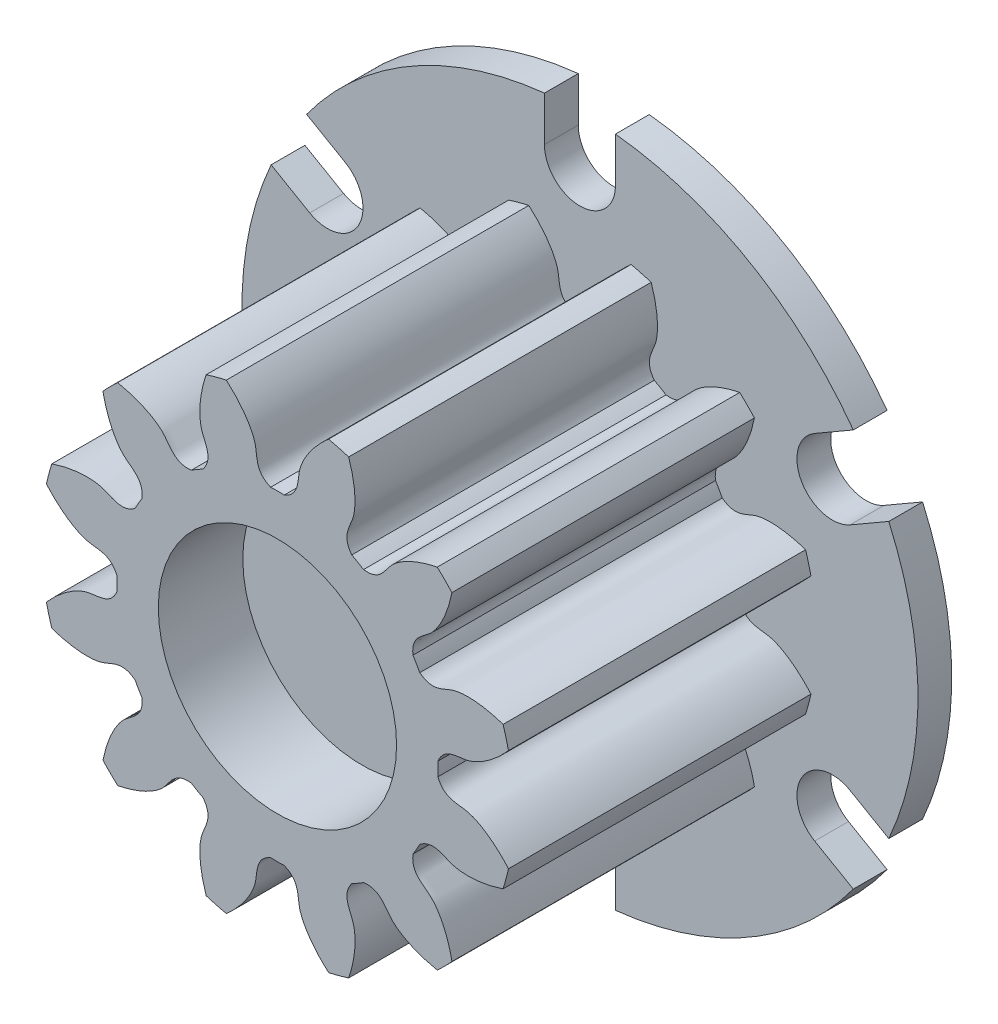
SolidWorks part; units mm, degrees
ref_plane "前视基准面" through (0, 0, 0) normal (0, 0, 1) x (1, 0, 0)
ref_plane "上视基准面" through (0, 0, 0) normal (0, 1, 0) x (1, 0, 0)
ref_plane "右视基准面" through (0, 0, 0) normal (1, 0, 0) x (0, 0, -1)
sketch "草图1" plane through (0, 0, 0) normal (0, 0, 1) x (1, 0, 0)
  circle A0 centre (0, 0) radius 14
extrude "凸台-拉伸1" add sketch "草图1" along normal blind 17.9
ref_axis "基准轴1" through (0, 0, -0.6) along (0, 0, 1)
sketch "草图2" plane through (0, 0, 0) normal (0, 0, 1) x (1, 0, 0)
  line L0 (0, 0) -> (0, 14) construction
  circle A0 centre (0, 0) radius 14 construction
  arc A1 (0.4017, 9.4915) -> (-0.4017, 9.4915) centre (0, 0) ccw
  arc A2 (6.9952, 15.7899) -> (-6.9952, 15.7899) centre (0, 0) ccw
  spline S0 degree 3 poles (0.4017, 9.4915) (1.3616, 9.8986) (1.1487, 10.6896) (1.3523, 11.379) (1.3652, 11.4198) (1.3805, 11.4647) (1.3981, 11.5135) (1.4183, 11.5661) (1.4413, 11.6225) (1.4671, 11.6826) (1.4961, 11.7462) (1.5282, 11.8133) (1.5637, 11.8838) (1.6028, 11.9576) (1.6455, 12.0345) (1.6919, 12.1144) (1.7423, 12.1973) (1.7968, 12.2829) (1.8555, 12.3712) (1.9185, 12.462) (1.9859, 12.5552) (2.0579, 12.6506) (2.1346, 12.7481) (2.2161, 12.8475) (2.3025, 12.9487) (2.3939, 13.0516) (2.4904, 13.1559) (2.5921, 13.2615) (2.6991, 13.3682) (2.8114, 13.4759) (2.9292, 13.5844) (3.0525, 13.6935) (3.1814, 13.803) (3.316, 13.9128) (3.4563, 14.0226) (3.6023, 14.1323) (3.7542, 14.2418) (3.912, 14.3507) (4.0756, 14.4589) (4.2452, 14.5663) (4.4208, 14.6726) (4.6024, 14.7776) (4.79, 14.8811) (4.9836, 14.983) (5.1832, 15.083) (5.3889, 15.1809) (5.6006, 15.2765) (5.8183, 15.3697) (6.042, 15.4602) (6.2717, 15.5478) (6.5888, 15.6615) (6.8312, 15.7402) (6.9952, 15.7899) knots 0 0 0 0 0.218015 0.222044 0.226546 0.231522 0.236972 0.242897 0.249295 0.256167 0.263513 0.271332 0.279626 0.288394 0.297636 0.307351 0.317541 0.328204 0.339341 0.350953 0.363038 0.375597 0.38863 0.402137 0.416118 0.430573 0.445502 0.460904 0.476781 0.493132 0.509956 0.527255 0.545027 0.563273 0.581994 0.601188 0.620856 0.640998 0.661614 0.682704 0.704268 0.726305 0.748817 0.771803 0.795262 0.819196 0.843603 0.868484 0.89384 0.919669 0.945972 1 1 1 1
  spline S1 degree 3 poles (-0.4017, 9.4915) (-1.3616, 9.8986) (-1.1487, 10.6896) (-1.3523, 11.379) (-1.3652, 11.4198) (-1.3805, 11.4647) (-1.3981, 11.5135) (-1.4183, 11.5661) (-1.4413, 11.6225) (-1.4671, 11.6826) (-1.4961, 11.7462) (-1.5282, 11.8133) (-1.5637, 11.8838) (-1.6028, 11.9576) (-1.6455, 12.0345) (-1.6919, 12.1144) (-1.7423, 12.1973) (-1.7968, 12.2829) (-1.8555, 12.3712) (-1.9185, 12.462) (-1.9859, 12.5552) (-2.0579, 12.6506) (-2.1346, 12.7481) (-2.2161, 12.8475) (-2.3025, 12.9487) (-2.3939, 13.0516) (-2.4904, 13.1559) (-2.5921, 13.2615) (-2.6991, 13.3682) (-2.8114, 13.4759) (-2.9292, 13.5844) (-3.0525, 13.6935) (-3.1814, 13.803) (-3.316, 13.9128) (-3.4563, 14.0226) (-3.6023, 14.1323) (-3.7542, 14.2418) (-3.912, 14.3507) (-4.0756, 14.4589) (-4.2452, 14.5663) (-4.4208, 14.6726) (-4.6024, 14.7776) (-4.79, 14.8811) (-4.9836, 14.983) (-5.1832, 15.083) (-5.3889, 15.1809) (-5.6006, 15.2765) (-5.8183, 15.3697) (-6.042, 15.4602) (-6.2717, 15.5478) (-6.5888, 15.6615) (-6.8312, 15.7402) (-6.9952, 15.7899) knots 0 0 0 0 0.218015 0.222044 0.226546 0.231522 0.236972 0.242897 0.249295 0.256167 0.263513 0.271332 0.279626 0.288394 0.297636 0.307351 0.317541 0.328204 0.339341 0.350953 0.363038 0.375597 0.38863 0.402137 0.416118 0.430573 0.445502 0.460904 0.476781 0.493132 0.509956 0.527255 0.545027 0.563273 0.581994 0.601188 0.620856 0.640998 0.661614 0.682704 0.704268 0.726305 0.748817 0.771803 0.795262 0.819196 0.843603 0.868484 0.89384 0.919669 0.945972 1 1 1 1
extrude "切除-拉伸1" cut sketch "草图2" along normal through all
pattern_circular "阵列(圆周)1" count 12 every 30 about axis through (0, 0, -0.6) along (0, 0, 1) of "切除-拉伸1"
sketch "草图3" plane through (0, 0, 0) normal (0, 0, 1) x (1, 0, 0)
  circle A0 centre (0, 0) radius 12 construction
  dimension "Dn" = 24
sketch "草图4" plane through (0, 0, 0) normal (0, 0, -1) x (-1, 0, 0)
  circle A0 centre (0, 0) radius 7.5
  dimension "D1" = 15
extrude "凸台-拉伸2" add sketch "草图4" along normal blind 2 contours A0
sketch "草图5" plane through (0, 0, -2) normal (0, 0, -1) x (-1, 0, 0)
  line L0 (2.1, 17.25) -> (2.1, 19.8894)
  line L1 (0, 0) -> (0, 17.25) construction
  line L2 (-2.1, 17.25) -> (-2.1, 19.8894)
  line L3 (13.8889, 10.4437) -> (16.1748, 11.7634)
  line L4 (15.9889, 6.8063) -> (18.2748, 8.1261)
  line L5 (15.9889, -6.8063) -> (18.2748, -8.1261)
  line L6 (13.8889, -10.4437) -> (16.1748, -11.7634)
  line L7 (2.1, -17.25) -> (2.1, -19.8894)
  line L8 (-2.1, -17.25) -> (-2.1, -19.8894)
  line L9 (-13.8889, -10.4437) -> (-16.1748, -11.7634)
  line L10 (-15.9889, -6.8063) -> (-18.2748, -8.1261)
  line L11 (-15.9889, 6.8063) -> (-18.2748, 8.1261)
  line L12 (-13.8889, 10.4437) -> (-16.1748, 11.7634)
  circle A0 centre (0, 0) radius 17.25 construction
  circle A1 centre (0, 0) radius 20
  circle A2 centre (0, 17.25) radius 2.1
  circle A3 centre (14.9389, 8.625) radius 2.1
  circle A4 centre (14.9389, -8.625) radius 2.1
  circle A5 centre (0, -17.25) radius 2.1
  circle A6 centre (-14.9389, -8.625) radius 2.1
  circle A7 centre (-14.9389, 8.625) radius 2.1
  point P18 (0, 0)
  point P44 (0, 0)
  circle M10 centre (0, 0) radius 7.5
  dimension "D1" = 34.5
  dimension "D2" = 40
  dimension "D3" = 4.2
  dimension "D4" = 6
  dimension "D5" = 6
extrude "凸台-拉伸3" [suppressed] add sketch "草图5" along normal blind 2 contours A7 L11 A1 L10 A6 L9 L8 A5 L7 L6 A4 L5 L4 A3 L3 L0 A2 L2 L12 M10 | M10
sketch "草图6" plane through (0, 0, 17.9) normal (0, 0, 1) x (1, 0, 0)
  circle A0 centre (0, 0) radius 7.05
  arc A24 (-4.3979, 8.4207) -> (-5.0936, 8.019) centre (0, 0) ccw
  arc A25 (-9.4547, 10.3251) -> (-10.3251, 9.4547) centre (0, 0) ccw
  arc A26 (-8.019, 5.0936) -> (-8.4207, 4.3979) centre (0, 0) ccw
  arc A27 (-13.3506, 4.2145) -> (-13.6692, 3.0255) centre (0, 0) ccw
  arc A28 (-9.4915, 0.4017) -> (-9.4915, -0.4017) centre (0, 0) ccw
  arc A29 (-13.6692, -3.0255) -> (-13.3506, -4.2145) centre (0, 0) ccw
  arc A30 (-8.4207, -4.3979) -> (-8.019, -5.0936) centre (0, 0) ccw
  arc A31 (-10.3251, -9.4547) -> (-9.4547, -10.3251) centre (0, 0) ccw
  arc A32 (-5.0936, -8.019) -> (-4.3979, -8.4207) centre (0, 0) ccw
  arc A33 (-4.2145, -13.3506) -> (-3.0255, -13.6692) centre (0, 0) ccw
  arc A34 (-0.4017, -9.4915) -> (0.4017, -9.4915) centre (0, 0) ccw
  arc A35 (3.0255, -13.6692) -> (4.2145, -13.3506) centre (0, 0) ccw
  arc A36 (4.3979, -8.4207) -> (5.0936, -8.019) centre (0, 0) ccw
  arc A37 (9.4547, -10.3251) -> (10.3251, -9.4547) centre (0, 0) ccw
  arc A38 (8.019, -5.0936) -> (8.4207, -4.3979) centre (0, 0) ccw
  arc A39 (13.3506, -4.2145) -> (13.6692, -3.0255) centre (0, 0) ccw
  arc A40 (9.4915, -0.4017) -> (9.4915, 0.4017) centre (0, 0) ccw
  arc A41 (13.6692, 3.0255) -> (13.3506, 4.2145) centre (0, 0) ccw
  arc A42 (8.4207, 4.3979) -> (8.019, 5.0936) centre (0, 0) ccw
  arc A43 (10.3251, 9.4547) -> (9.4547, 10.3251) centre (0, 0) ccw
  arc A44 (5.0936, 8.019) -> (4.3979, 8.4207) centre (0, 0) ccw
  arc A45 (4.2145, 13.3506) -> (3.0255, 13.6692) centre (0, 0) ccw
  arc A46 (0.4017, 9.4915) -> (-0.4017, 9.4915) centre (0, 0) ccw
  arc A47 (-3.0255, 13.6692) -> (-4.2145, 13.3506) centre (0, 0) ccw
  arc A48 (-4.3979, 8.4207) -> (-5.0936, 8.019) centre (0, 0) ccw
  arc A49 (-9.4547, 10.3251) -> (-10.3251, 9.4547) centre (0, 0) ccw
  arc A50 (-8.019, 5.0936) -> (-8.4207, 4.3979) centre (0, 0) ccw
  arc A51 (-13.3506, 4.2145) -> (-13.6692, 3.0255) centre (0, 0) ccw
  arc A52 (-9.4915, 0.4017) -> (-9.4915, -0.4017) centre (0, 0) ccw
  arc A53 (-13.6692, -3.0255) -> (-13.3506, -4.2145) centre (0, 0) ccw
  arc A54 (-8.4207, -4.3979) -> (-8.019, -5.0936) centre (0, 0) ccw
  arc A55 (-10.3251, -9.4547) -> (-9.4547, -10.3251) centre (0, 0) ccw
  arc A56 (-5.0936, -8.019) -> (-4.3979, -8.4207) centre (0, 0) ccw
  arc A57 (-4.2145, -13.3506) -> (-3.0255, -13.6692) centre (0, 0) ccw
  arc A58 (-0.4017, -9.4915) -> (0.4017, -9.4915) centre (0, 0) ccw
  arc A59 (3.0255, -13.6692) -> (4.2145, -13.3506) centre (0, 0) ccw
  arc A60 (4.3979, -8.4207) -> (5.0936, -8.019) centre (0, 0) ccw
  arc A61 (9.4547, -10.3251) -> (10.3251, -9.4547) centre (0, 0) ccw
  arc A62 (8.019, -5.0936) -> (8.4207, -4.3979) centre (0, 0) ccw
  arc A63 (13.3506, -4.2145) -> (13.6692, -3.0255) centre (0, 0) ccw
  arc A64 (9.4915, -0.4017) -> (9.4915, 0.4017) centre (0, 0) ccw
  arc A65 (13.6692, 3.0255) -> (13.3506, 4.2145) centre (0, 0) ccw
  arc A66 (8.4207, 4.3979) -> (8.019, 5.0936) centre (0, 0) ccw
  arc A67 (10.3251, 9.4547) -> (9.4547, 10.3251) centre (0, 0) ccw
  arc A68 (5.0936, 8.019) -> (4.3979, 8.4207) centre (0, 0) ccw
  arc A69 (4.2145, 13.3506) -> (3.0255, 13.6692) centre (0, 0) ccw
  arc A70 (0.4017, 9.4915) -> (-0.4017, 9.4915) centre (0, 0) ccw
  arc A71 (-3.0255, 13.6692) -> (-4.2145, 13.3506) centre (0, 0) ccw
  spline S24 degree 3 poles (2052.1623, 2191.1493) (-39.4787, -48.9387) (-0.5786, 3.2069) (-6.8721, 9.1892) (-6.9309, 9.2418) (-7.0145, 9.3106) (-7.1151, 9.387) (-7.2335, 9.4697) (-7.3702, 9.5573) (-7.5259, 9.6485) (-7.7011, 9.7419) (-7.8961, 9.8361) (-8.1112, 9.9296) (-8.3468, 10.021) (-8.6028, 10.1087) (-8.8795, 10.1914) (-39.0749, 17.9093) (-111.0172, -152.8208) (2365.5035, 1842.2647) knots -2.028933 -2.028933 -2.028933 -2.028933 0.69442 0.698448 0.707927 0.719301 0.732571 0.747737 0.764798 0.783756 0.804608 0.827357 0.852001 0.878542 0.906977 0.937309 0.969536 10.7291 10.7291 10.7291 10.7291 only from (-5.0936, 8.019) to (-9.4547, 10.3251)
  spline S25 degree 3 poles (-1837.9661, -2368.8794) (150.6443, 113.0421) (-18.3423, 38.3111) (-10.1508, 8.7386) (-10.0654, 8.4722) (-9.9757, 8.2264) (-9.883, 8.0011) (-9.789, 7.7961) (-9.695, 7.6111) (-9.6025, 7.4457) (-9.5129, 7.2995) (-9.4276, 7.172) (-9.359, 7.0778) (-9.2968, 6.9977) (-9.2418, 6.9309) (-9.1892, 6.8721) (-3.2069, 0.5786) (48.9386, 39.4786) (-2191.1398, -2052.1534) knots -9.563336 -9.563336 -9.563336 -9.563336 0.046814 0.078094 0.107478 0.134965 0.160558 0.184254 0.206055 0.22596 0.243969 0.260083 0.274301 0.280699 0.292073 0.301552 0.30558 3.02893 3.02893 3.02893 3.02893 only from (-10.3251, 9.4547) to (-8.019, 5.0936)
  spline S26 degree 3 poles (681.6501, 2923.6721) (-9.7202, -62.1215) (-2.1045, 2.4879) (-10.546, 4.522) (-10.6233, 4.5381) (-10.7301, 4.556) (-10.8554, 4.5718) (-10.9992, 4.5842) (-11.1614, 4.5917) (-11.3419, 4.5929) (-11.5403, 4.5862) (-11.7563, 4.5702) (-11.9893, 4.5437) (-12.239, 4.505) (-12.5046, 4.453) (-12.7855, 4.3862) (-42.7945, -4.0276) (-19.7333, -187.8553) (1127.4538, 2778.1998) knots -2.028933 -2.028933 -2.028933 -2.028933 0.69442 0.698448 0.707927 0.719301 0.732571 0.747737 0.764798 0.783756 0.804608 0.827357 0.852001 0.878542 0.906977 0.937309 0.969536 10.7291 10.7291 10.7291 10.7291 only from (-8.4207, 4.3979) to (-13.3506, 4.2145)
  spline S27 degree 3 poles (-407.2856, -2970.4928) (73.9407, 173.2195) (-35.0405, 24.0073) (-13.1601, 2.4924) (-12.953, 2.3045) (-12.7524, 2.1365) (-12.5595, 1.9877) (-12.3755, 1.8571) (-12.2016, 1.7439) (-12.0389, 1.6469) (-11.8882, 1.5651) (-11.7506, 1.4973) (-11.6441, 1.4501) (-11.5501, 1.4118) (-11.4691, 1.3815) (-11.3941, 1.3568) (-3.0665, -1.1024) (22.6428, 58.6587) (-871.506, -2872.7869) knots -9.563336 -9.563336 -9.563336 -9.563336 0.046814 0.078094 0.107478 0.134965 0.160558 0.184254 0.206055 0.22596 0.243969 0.260083 0.274301 0.280699 0.292073 0.301552 0.30558 3.02893 3.02893 3.02893 3.02893 only from (-13.6692, 3.0255) to (-9.4915, 0.4017)
  spline S28 degree 3 poles (-871.5098, 2872.7993) (22.6429, -58.6589) (-3.0665, 1.1024) (-11.3941, -1.3568) (-11.4691, -1.3815) (-11.5705, -1.4194) (-11.687, -1.4684) (-11.8177, -1.5295) (-11.962, -1.6042) (-12.1188, -1.6934) (-12.2873, -1.7984) (-12.4663, -1.9202) (-12.6549, -2.0597) (-12.8518, -2.218) (-13.0558, -2.3959) (-13.2657, -2.5942) (-35.0474, -24.8852) (76.8381, -172.5541) (-412.6963, 2969.7185) knots -2.028933 -2.028933 -2.028933 -2.028933 0.69442 0.698448 0.707927 0.719301 0.732571 0.747737 0.764798 0.783756 0.804608 0.827357 0.852001 0.878542 0.906977 0.937309 0.969536 10.7291 10.7291 10.7291 10.7291 only from (-9.4915, -0.4017) to (-13.6692, -3.0255)
  spline S29 degree 3 poles (1132.5267, -2776.1651) (-22.5752, 186.9828) (-42.3496, 3.2707) (-12.6432, -4.4215) (-12.3699, -4.4808) (-12.1121, -4.5259) (-11.8707, -4.5584) (-11.6461, -4.5794) (-11.4389, -4.5906) (-11.2494, -4.5932) (-11.078, -4.5887) (-10.925, -4.5786) (-10.8091, -4.5662) (-10.7085, -4.5524) (-10.6233, -4.5381) (-10.546, -4.522) (-2.1045, -2.4879) (-9.7201, 62.1214) (681.6471, -2923.6594) knots -9.563336 -9.563336 -9.563336 -9.563336 0.046814 0.078094 0.107478 0.134965 0.160558 0.184254 0.206055 0.22596 0.243969 0.260083 0.274301 0.280699 0.292073 0.301552 0.30558 3.02893 3.02893 3.02893 3.02893 only from (-13.3506, -4.2145) to (-8.4207, -4.3979)
  spline S30 degree 3 poles (-2191.1493, 2052.1623) (48.9387, -39.4787) (-3.2069, -0.5786) (-9.1892, -6.8721) (-9.2418, -6.9309) (-9.3106, -7.0145) (-9.387, -7.1151) (-9.4697, -7.2335) (-9.5573, -7.3702) (-9.6485, -7.5259) (-9.7419, -7.7011) (-9.8361, -7.8961) (-9.9296, -8.1112) (-10.021, -8.3468) (-10.1087, -8.6028) (-10.1914, -8.8795) (-17.9093, -39.0749) (152.8208, -111.0172) (-1842.2647, 2365.5035) knots -2.028933 -2.028933 -2.028933 -2.028933 0.69442 0.698448 0.707927 0.719301 0.732571 0.747737 0.764798 0.783756 0.804608 0.827357 0.852001 0.878542 0.906977 0.937309 0.969536 10.7291 10.7291 10.7291 10.7291 only from (-8.019, -5.0936) to (-10.3251, -9.4547)
  spline S31 degree 3 poles (2368.8794, -1837.9661) (-113.0421, 150.6443) (-38.3111, -18.3423) (-8.7386, -10.1508) (-8.4722, -10.0654) (-8.2264, -9.9757) (-8.0011, -9.883) (-7.7961, -9.789) (-7.6111, -9.695) (-7.4457, -9.6025) (-7.2995, -9.5129) (-7.172, -9.4276) (-7.0778, -9.359) (-6.9977, -9.2968) (-6.9309, -9.2418) (-6.8721, -9.1892) (-0.5786, -3.2069) (-39.4786, 48.9386) (2052.1534, -2191.1398) knots -9.563336 -9.563336 -9.563336 -9.563336 0.046814 0.078094 0.107478 0.134965 0.160558 0.184254 0.206055 0.22596 0.243969 0.260083 0.274301 0.280699 0.292073 0.301552 0.30558 3.02893 3.02893 3.02893 3.02893 only from (-9.4547, -10.3251) to (-5.0936, -8.019)
  spline S32 degree 3 poles (-2923.6721, 681.6501) (62.1215, -9.7202) (-2.4879, -2.1045) (-4.522, -10.546) (-4.5381, -10.6233) (-4.556, -10.7301) (-4.5718, -10.8554) (-4.5842, -10.9992) (-4.5917, -11.1614) (-4.5929, -11.3419) (-4.5862, -11.5403) (-4.5702, -11.7563) (-4.5437, -11.9893) (-4.505, -12.239) (-4.453, -12.5046) (-4.3862, -12.7855) (4.0276, -42.7945) (187.8553, -19.7333) (-2778.1998, 1127.4538) knots -2.028933 -2.028933 -2.028933 -2.028933 0.69442 0.698448 0.707927 0.719301 0.732571 0.747737 0.764798 0.783756 0.804608 0.827357 0.852001 0.878542 0.906977 0.937309 0.969536 10.7291 10.7291 10.7291 10.7291 only from (-4.3979, -8.4207) to (-4.2145, -13.3506)
  spline S33 degree 3 poles (2970.4928, -407.2856) (-173.2195, 73.9407) (-24.0073, -35.0405) (-2.4924, -13.1601) (-2.3045, -12.953) (-2.1365, -12.7524) (-1.9877, -12.5595) (-1.8571, -12.3755) (-1.7439, -12.2016) (-1.6469, -12.0389) (-1.5651, -11.8882) (-1.4973, -11.7506) (-1.4501, -11.6441) (-1.4118, -11.5501) (-1.3815, -11.4691) (-1.3568, -11.3941) (1.1024, -3.0665) (-58.6587, 22.6428) (2872.7869, -871.506) knots -9.563336 -9.563336 -9.563336 -9.563336 0.046814 0.078094 0.107478 0.134965 0.160558 0.184254 0.206055 0.22596 0.243969 0.260083 0.274301 0.280699 0.292073 0.301552 0.30558 3.02893 3.02893 3.02893 3.02893 only from (-3.0255, -13.6692) to (-0.4017, -9.4915)
  spline S34 degree 3 poles (-2872.7993, -871.5098) (58.6589, 22.6429) (-1.1024, -3.0665) (1.3568, -11.3941) (1.3815, -11.4691) (1.4194, -11.5705) (1.4684, -11.687) (1.5295, -11.8177) (1.6042, -11.962) (1.6934, -12.1188) (1.7984, -12.2873) (1.9202, -12.4663) (2.0597, -12.6549) (2.218, -12.8518) (2.3959, -13.0558) (2.5942, -13.2657) (24.8852, -35.0474) (172.5541, 76.8381) (-2969.7185, -412.6963) knots -2.028933 -2.028933 -2.028933 -2.028933 0.69442 0.698448 0.707927 0.719301 0.732571 0.747737 0.764798 0.783756 0.804608 0.827357 0.852001 0.878542 0.906977 0.937309 0.969536 10.7291 10.7291 10.7291 10.7291 only from (0.4017, -9.4915) to (3.0255, -13.6692)
  spline S35 degree 3 poles (2776.1651, 1132.5267) (-186.9828, -22.5752) (-3.2707, -42.3496) (4.4215, -12.6432) (4.4808, -12.3699) (4.5259, -12.1121) (4.5584, -11.8707) (4.5794, -11.6461) (4.5906, -11.4389) (4.5932, -11.2494) (4.5887, -11.078) (4.5786, -10.925) (4.5662, -10.8091) (4.5524, -10.7085) (4.5381, -10.6233) (4.522, -10.546) (2.4879, -2.1045) (-62.1214, -9.7201) (2923.6594, 681.6471) knots -9.563336 -9.563336 -9.563336 -9.563336 0.046814 0.078094 0.107478 0.134965 0.160558 0.184254 0.206055 0.22596 0.243969 0.260083 0.274301 0.280699 0.292073 0.301552 0.30558 3.02893 3.02893 3.02893 3.02893 only from (4.2145, -13.3506) to (4.3979, -8.4207)
  spline S36 degree 3 poles (-2052.1623, -2191.1493) (39.4787, 48.9387) (0.5786, -3.2069) (6.8721, -9.1892) (6.9309, -9.2418) (7.0145, -9.3106) (7.1151, -9.387) (7.2335, -9.4697) (7.3702, -9.5573) (7.5259, -9.6485) (7.7011, -9.7419) (7.8961, -9.8361) (8.1112, -9.9296) (8.3468, -10.021) (8.6028, -10.1087) (8.8795, -10.1914) (39.0749, -17.9093) (111.0172, 152.8208) (-2365.5035, -1842.2647) knots -2.028933 -2.028933 -2.028933 -2.028933 0.69442 0.698448 0.707927 0.719301 0.732571 0.747737 0.764798 0.783756 0.804608 0.827357 0.852001 0.878542 0.906977 0.937309 0.969536 10.7291 10.7291 10.7291 10.7291 only from (5.0936, -8.019) to (9.4547, -10.3251)
  spline S37 degree 3 poles (1837.9661, 2368.8794) (-150.6443, -113.0421) (18.3423, -38.3111) (10.1508, -8.7386) (10.0654, -8.4722) (9.9757, -8.2264) (9.883, -8.0011) (9.789, -7.7961) (9.695, -7.6111) (9.6025, -7.4457) (9.5129, -7.2995) (9.4276, -7.172) (9.359, -7.0778) (9.2968, -6.9977) (9.2418, -6.9309) (9.1892, -6.8721) (3.2069, -0.5786) (-48.9386, -39.4786) (2191.1398, 2052.1534) knots -9.563336 -9.563336 -9.563336 -9.563336 0.046814 0.078094 0.107478 0.134965 0.160558 0.184254 0.206055 0.22596 0.243969 0.260083 0.274301 0.280699 0.292073 0.301552 0.30558 3.02893 3.02893 3.02893 3.02893 only from (10.3251, -9.4547) to (8.019, -5.0936)
  spline S38 degree 3 poles (-681.6501, -2923.6721) (9.7202, 62.1215) (2.1045, -2.4879) (10.546, -4.522) (10.6233, -4.5381) (10.7301, -4.556) (10.8554, -4.5718) (10.9992, -4.5842) (11.1614, -4.5917) (11.3419, -4.5929) (11.5403, -4.5862) (11.7563, -4.5702) (11.9893, -4.5437) (12.239, -4.505) (12.5046, -4.453) (12.7855, -4.3862) (42.7945, 4.0276) (19.7333, 187.8553) (-1127.4538, -2778.1998) knots -2.028933 -2.028933 -2.028933 -2.028933 0.69442 0.698448 0.707927 0.719301 0.732571 0.747737 0.764798 0.783756 0.804608 0.827357 0.852001 0.878542 0.906977 0.937309 0.969536 10.7291 10.7291 10.7291 10.7291 only from (8.4207, -4.3979) to (13.3506, -4.2145)
  spline S39 degree 3 poles (407.2856, 2970.4928) (-73.9407, -173.2195) (35.0405, -24.0073) (13.1601, -2.4924) (12.953, -2.3045) (12.7524, -2.1365) (12.5595, -1.9877) (12.3755, -1.8571) (12.2016, -1.7439) (12.0389, -1.6469) (11.8882, -1.5651) (11.7506, -1.4973) (11.6441, -1.4501) (11.5501, -1.4118) (11.4691, -1.3815) (11.3941, -1.3568) (3.0665, 1.1024) (-22.6428, -58.6587) (871.506, 2872.7869) knots -9.563336 -9.563336 -9.563336 -9.563336 0.046814 0.078094 0.107478 0.134965 0.160558 0.184254 0.206055 0.22596 0.243969 0.260083 0.274301 0.280699 0.292073 0.301552 0.30558 3.02893 3.02893 3.02893 3.02893 only from (13.6692, -3.0255) to (9.4915, -0.4017)
  spline S40 degree 3 poles (871.5098, -2872.7993) (-22.6429, 58.6589) (3.0665, -1.1024) (11.3941, 1.3568) (11.4691, 1.3815) (11.5705, 1.4194) (11.687, 1.4684) (11.8177, 1.5295) (11.962, 1.6042) (12.1188, 1.6934) (12.2873, 1.7984) (12.4663, 1.9202) (12.6549, 2.0597) (12.8518, 2.218) (13.0558, 2.3959) (13.2657, 2.5942) (35.0474, 24.8852) (-76.8381, 172.5541) (412.6963, -2969.7185) knots -2.028933 -2.028933 -2.028933 -2.028933 0.69442 0.698448 0.707927 0.719301 0.732571 0.747737 0.764798 0.783756 0.804608 0.827357 0.852001 0.878542 0.906977 0.937309 0.969536 10.7291 10.7291 10.7291 10.7291 only from (9.4915, 0.4017) to (13.6692, 3.0255)
  spline S41 degree 3 poles (-1132.5267, 2776.1651) (22.5752, -186.9828) (42.3496, -3.2707) (12.6432, 4.4215) (12.3699, 4.4808) (12.1121, 4.5259) (11.8707, 4.5584) (11.6461, 4.5794) (11.4389, 4.5906) (11.2494, 4.5932) (11.078, 4.5887) (10.925, 4.5786) (10.8091, 4.5662) (10.7085, 4.5524) (10.6233, 4.5381) (10.546, 4.522) (2.1045, 2.4879) (9.7201, -62.1214) (-681.6471, 2923.6594) knots -9.563336 -9.563336 -9.563336 -9.563336 0.046814 0.078094 0.107478 0.134965 0.160558 0.184254 0.206055 0.22596 0.243969 0.260083 0.274301 0.280699 0.292073 0.301552 0.30558 3.02893 3.02893 3.02893 3.02893 only from (13.3506, 4.2145) to (8.4207, 4.3979)
  spline S42 degree 3 poles (2191.1493, -2052.1623) (-48.9387, 39.4787) (3.2069, 0.5786) (9.1892, 6.8721) (9.2418, 6.9309) (9.3106, 7.0145) (9.387, 7.1151) (9.4697, 7.2335) (9.5573, 7.3702) (9.6485, 7.5259) (9.7419, 7.7011) (9.8361, 7.8961) (9.9296, 8.1112) (10.021, 8.3468) (10.1087, 8.6028) (10.1914, 8.8795) (17.9093, 39.0749) (-152.8208, 111.0172) (1842.2647, -2365.5035) knots -2.028933 -2.028933 -2.028933 -2.028933 0.69442 0.698448 0.707927 0.719301 0.732571 0.747737 0.764798 0.783756 0.804608 0.827357 0.852001 0.878542 0.906977 0.937309 0.969536 10.7291 10.7291 10.7291 10.7291 only from (8.019, 5.0936) to (10.3251, 9.4547)
  spline S43 degree 3 poles (-2368.8794, 1837.9661) (113.0421, -150.6443) (38.3111, 18.3423) (8.7386, 10.1508) (8.4722, 10.0654) (8.2264, 9.9757) (8.0011, 9.883) (7.7961, 9.789) (7.6111, 9.695) (7.4457, 9.6025) (7.2995, 9.5129) (7.172, 9.4276) (7.0778, 9.359) (6.9977, 9.2968) (6.9309, 9.2418) (6.8721, 9.1892) (0.5786, 3.2069) (39.4786, -48.9386) (-2052.1534, 2191.1398) knots -9.563336 -9.563336 -9.563336 -9.563336 0.046814 0.078094 0.107478 0.134965 0.160558 0.184254 0.206055 0.22596 0.243969 0.260083 0.274301 0.280699 0.292073 0.301552 0.30558 3.02893 3.02893 3.02893 3.02893 only from (9.4547, 10.3251) to (5.0936, 8.019)
  spline S44 degree 3 poles (2923.6721, -681.6501) (-62.1215, 9.7202) (2.4879, 2.1045) (4.522, 10.546) (4.5381, 10.6233) (4.556, 10.7301) (4.5718, 10.8554) (4.5842, 10.9992) (4.5917, 11.1614) (4.5929, 11.3419) (4.5862, 11.5403) (4.5702, 11.7563) (4.5437, 11.9893) (4.505, 12.239) (4.453, 12.5046) (4.3862, 12.7855) (-4.0276, 42.7945) (-187.8553, 19.7333) (2778.1998, -1127.4538) knots -2.028933 -2.028933 -2.028933 -2.028933 0.69442 0.698448 0.707927 0.719301 0.732571 0.747737 0.764798 0.783756 0.804608 0.827357 0.852001 0.878542 0.906977 0.937309 0.969536 10.7291 10.7291 10.7291 10.7291 only from (4.3979, 8.4207) to (4.2145, 13.3506)
  spline S45 degree 3 poles (-2970.4928, 407.2856) (173.2195, -73.9407) (24.0073, 35.0405) (2.4924, 13.1601) (2.3045, 12.953) (2.1365, 12.7524) (1.9877, 12.5595) (1.8571, 12.3755) (1.7439, 12.2016) (1.6469, 12.0389) (1.5651, 11.8882) (1.4973, 11.7506) (1.4501, 11.6441) (1.4118, 11.5501) (1.3815, 11.4691) (1.3568, 11.3941) (-1.1024, 3.0665) (58.6587, -22.6428) (-2872.7869, 871.506) knots -9.563336 -9.563336 -9.563336 -9.563336 0.046814 0.078094 0.107478 0.134965 0.160558 0.184254 0.206055 0.22596 0.243969 0.260083 0.274301 0.280699 0.292073 0.301552 0.30558 3.02893 3.02893 3.02893 3.02893 only from (3.0255, 13.6692) to (0.4017, 9.4915)
  spline S46 degree 3 poles (2872.7993, 871.5098) (-58.6589, -22.6429) (1.1024, 3.0665) (-1.3568, 11.3941) (-1.3815, 11.4691) (-1.4194, 11.5705) (-1.4684, 11.687) (-1.5295, 11.8177) (-1.6042, 11.962) (-1.6934, 12.1188) (-1.7984, 12.2873) (-1.9202, 12.4663) (-2.0597, 12.6549) (-2.218, 12.8518) (-2.3959, 13.0558) (-2.5942, 13.2657) (-24.8852, 35.0474) (-172.5541, -76.8381) (2969.7185, 412.6963) knots -2.028933 -2.028933 -2.028933 -2.028933 0.69442 0.698448 0.707927 0.719301 0.732571 0.747737 0.764798 0.783756 0.804608 0.827357 0.852001 0.878542 0.906977 0.937309 0.969536 10.7291 10.7291 10.7291 10.7291 only from (-0.4017, 9.4915) to (-3.0255, 13.6692)
  spline S47 degree 3 poles (-2776.1651, -1132.5267) (186.9828, 22.5752) (3.2707, 42.3496) (-4.4215, 12.6432) (-4.4808, 12.3699) (-4.5259, 12.1121) (-4.5584, 11.8707) (-4.5794, 11.6461) (-4.5906, 11.4389) (-4.5932, 11.2494) (-4.5887, 11.078) (-4.5786, 10.925) (-4.5662, 10.8091) (-4.5524, 10.7085) (-4.5381, 10.6233) (-4.522, 10.546) (-2.4879, 2.1045) (62.1214, 9.7201) (-2923.6594, -681.6471) knots -9.563336 -9.563336 -9.563336 -9.563336 0.046814 0.078094 0.107478 0.134965 0.160558 0.184254 0.206055 0.22596 0.243969 0.260083 0.274301 0.280699 0.292073 0.301552 0.30558 3.02893 3.02893 3.02893 3.02893 only from (-4.2145, 13.3506) to (-4.3979, 8.4207)
  spline S48 degree 3 poles (-5.0936, 8.019) (-6.1285, 7.8917) (-6.3397, 8.6831) (-6.8721, 9.1892) (-6.9309, 9.2418) (-7.0145, 9.3106) (-7.1151, 9.387) (-7.2335, 9.4697) (-7.3702, 9.5573) (-7.5259, 9.6485) (-7.7011, 9.7419) (-7.8961, 9.8361) (-8.1112, 9.9296) (-8.3468, 10.021) (-8.6028, 10.1087) (-8.8795, 10.1914) (-9.1655, 10.2645) (-9.3599, 10.3064) (-9.4547, 10.3251) knots 0.476404 0.476404 0.476404 0.476404 0.69442 0.698448 0.707927 0.719301 0.732571 0.747737 0.764798 0.783756 0.804608 0.827357 0.852001 0.878542 0.906977 0.937309 0.969536 1 1 1 1
  spline S49 degree 3 poles (-10.3251, 9.4547) (-10.2963, 9.309) (-10.2418, 9.0672) (-10.1508, 8.7386) (-10.0654, 8.4722) (-9.9757, 8.2264) (-9.883, 8.0011) (-9.789, 7.7961) (-9.695, 7.6111) (-9.6025, 7.4457) (-9.5129, 7.2995) (-9.4276, 7.172) (-9.359, 7.0778) (-9.2968, 6.9977) (-9.2418, 6.9309) (-9.1892, 6.8721) (-8.6831, 6.3397) (-7.8917, 6.1285) (-8.019, 5.0936) knots 0 0 0 0 0.046814 0.078094 0.107478 0.134965 0.160558 0.184254 0.206055 0.22596 0.243969 0.260083 0.274301 0.280699 0.292073 0.301552 0.30558 0.523596 0.523596 0.523596 0.523596
  spline S50 degree 3 poles (-8.4207, 4.3979) (-9.2532, 3.7701) (-9.8319, 4.35) (-10.546, 4.522) (-10.6233, 4.5381) (-10.7301, 4.556) (-10.8554, 4.5718) (-10.9992, 4.5842) (-11.1614, 4.5917) (-11.3419, 4.5929) (-11.5403, 4.5862) (-11.7563, 4.5702) (-11.9893, 4.5437) (-12.239, 4.505) (-12.5046, 4.453) (-12.7855, 4.3862) (-13.0698, 4.3065) (-13.2591, 4.2457) (-13.3506, 4.2145) knots 0.476404 0.476404 0.476404 0.476404 0.69442 0.698448 0.707927 0.719301 0.732571 0.747737 0.764798 0.783756 0.804608 0.827357 0.852001 0.878542 0.906977 0.937309 0.969536 1 1 1 1
  spline S51 degree 3 poles (-13.6692, 3.0255) (-13.5714, 2.9137) (-13.4033, 2.7316) (-13.1601, 2.4924) (-12.953, 2.3045) (-12.7524, 2.1365) (-12.5595, 1.9877) (-12.3755, 1.8571) (-12.2016, 1.7439) (-12.0389, 1.6469) (-11.8882, 1.5651) (-11.7506, 1.4973) (-11.6441, 1.4501) (-11.5501, 1.4118) (-11.4691, 1.3815) (-11.3941, 1.3568) (-10.6896, 1.1487) (-9.8986, 1.3616) (-9.4915, 0.4017) knots 0 0 0 0 0.046814 0.078094 0.107478 0.134965 0.160558 0.184254 0.206055 0.22596 0.243969 0.260083 0.274301 0.280699 0.292073 0.301552 0.30558 0.523596 0.523596 0.523596 0.523596
  spline S52 degree 3 poles (-9.4915, -0.4017) (-9.8986, -1.3616) (-10.6896, -1.1487) (-11.3941, -1.3568) (-11.4691, -1.3815) (-11.5705, -1.4194) (-11.687, -1.4684) (-11.8177, -1.5295) (-11.962, -1.6042) (-12.1188, -1.6934) (-12.2873, -1.7984) (-12.4663, -1.9202) (-12.6549, -2.0597) (-12.8518, -2.218) (-13.0558, -2.3959) (-13.2657, -2.5942) (-13.472, -2.8053) (-13.6056, -2.9527) (-13.6692, -3.0255) knots 0.476404 0.476404 0.476404 0.476404 0.69442 0.698448 0.707927 0.719301 0.732571 0.747737 0.764798 0.783756 0.804608 0.827357 0.852001 0.878542 0.906977 0.937309 0.969536 1 1 1 1
  spline S53 degree 3 poles (-13.3506, -4.2145) (-13.21, -4.2624) (-12.9734, -4.3361) (-12.6432, -4.4215) (-12.3699, -4.4808) (-12.1121, -4.5259) (-11.8707, -4.5584) (-11.6461, -4.5794) (-11.4389, -4.5906) (-11.2494, -4.5932) (-11.078, -4.5887) (-10.925, -4.5786) (-10.8091, -4.5662) (-10.7085, -4.5524) (-10.6233, -4.5381) (-10.546, -4.522) (-9.8319, -4.35) (-9.2532, -3.7701) (-8.4207, -4.3979) knots 0 0 0 0 0.046814 0.078094 0.107478 0.134965 0.160558 0.184254 0.206055 0.22596 0.243969 0.260083 0.274301 0.280699 0.292073 0.301552 0.30558 0.523596 0.523596 0.523596 0.523596
  spline S54 degree 3 poles (-8.019, -5.0936) (-7.8917, -6.1285) (-8.6831, -6.3397) (-9.1892, -6.8721) (-9.2418, -6.9309) (-9.3106, -7.0145) (-9.387, -7.1151) (-9.4697, -7.2335) (-9.5573, -7.3702) (-9.6485, -7.5259) (-9.7419, -7.7011) (-9.8361, -7.8961) (-9.9296, -8.1112) (-10.021, -8.3468) (-10.1087, -8.6028) (-10.1914, -8.8795) (-10.2645, -9.1655) (-10.3064, -9.3599) (-10.3251, -9.4547) knots 0.476404 0.476404 0.476404 0.476404 0.69442 0.698448 0.707927 0.719301 0.732571 0.747737 0.764798 0.783756 0.804608 0.827357 0.852001 0.878542 0.906977 0.937309 0.969536 1 1 1 1
  spline S55 degree 3 poles (-9.4547, -10.3251) (-9.309, -10.2963) (-9.0672, -10.2418) (-8.7386, -10.1508) (-8.4722, -10.0654) (-8.2264, -9.9757) (-8.0011, -9.883) (-7.7961, -9.789) (-7.6111, -9.695) (-7.4457, -9.6025) (-7.2995, -9.5129) (-7.172, -9.4276) (-7.0778, -9.359) (-6.9977, -9.2968) (-6.9309, -9.2418) (-6.8721, -9.1892) (-6.3397, -8.6831) (-6.1285, -7.8917) (-5.0936, -8.019) knots 0 0 0 0 0.046814 0.078094 0.107478 0.134965 0.160558 0.184254 0.206055 0.22596 0.243969 0.260083 0.274301 0.280699 0.292073 0.301552 0.30558 0.523596 0.523596 0.523596 0.523596
  spline S56 degree 3 poles (-4.3979, -8.4207) (-3.7701, -9.2532) (-4.35, -9.8319) (-4.522, -10.546) (-4.5381, -10.6233) (-4.556, -10.7301) (-4.5718, -10.8554) (-4.5842, -10.9992) (-4.5917, -11.1614) (-4.5929, -11.3419) (-4.5862, -11.5403) (-4.5702, -11.7563) (-4.5437, -11.9893) (-4.505, -12.239) (-4.453, -12.5046) (-4.3862, -12.7855) (-4.3065, -13.0698) (-4.2457, -13.2591) (-4.2145, -13.3506) knots 0.476404 0.476404 0.476404 0.476404 0.69442 0.698448 0.707927 0.719301 0.732571 0.747737 0.764798 0.783756 0.804608 0.827357 0.852001 0.878542 0.906977 0.937309 0.969536 1 1 1 1
  spline S57 degree 3 poles (-3.0255, -13.6692) (-2.9137, -13.5714) (-2.7316, -13.4033) (-2.4924, -13.1601) (-2.3045, -12.953) (-2.1365, -12.7524) (-1.9877, -12.5595) (-1.8571, -12.3755) (-1.7439, -12.2016) (-1.6469, -12.0389) (-1.5651, -11.8882) (-1.4973, -11.7506) (-1.4501, -11.6441) (-1.4118, -11.5501) (-1.3815, -11.4691) (-1.3568, -11.3941) (-1.1487, -10.6896) (-1.3616, -9.8986) (-0.4017, -9.4915) knots 0 0 0 0 0.046814 0.078094 0.107478 0.134965 0.160558 0.184254 0.206055 0.22596 0.243969 0.260083 0.274301 0.280699 0.292073 0.301552 0.30558 0.523596 0.523596 0.523596 0.523596
  spline S58 degree 3 poles (0.4017, -9.4915) (1.3616, -9.8986) (1.1487, -10.6896) (1.3568, -11.3941) (1.3815, -11.4691) (1.4194, -11.5705) (1.4684, -11.687) (1.5295, -11.8177) (1.6042, -11.962) (1.6934, -12.1188) (1.7984, -12.2873) (1.9202, -12.4663) (2.0597, -12.6549) (2.218, -12.8518) (2.3959, -13.0558) (2.5942, -13.2657) (2.8053, -13.472) (2.9527, -13.6056) (3.0255, -13.6692) knots 0.476404 0.476404 0.476404 0.476404 0.69442 0.698448 0.707927 0.719301 0.732571 0.747737 0.764798 0.783756 0.804608 0.827357 0.852001 0.878542 0.906977 0.937309 0.969536 1 1 1 1
  spline S59 degree 3 poles (4.2145, -13.3506) (4.2624, -13.21) (4.3361, -12.9734) (4.4215, -12.6432) (4.4808, -12.3699) (4.5259, -12.1121) (4.5584, -11.8707) (4.5794, -11.6461) (4.5906, -11.4389) (4.5932, -11.2494) (4.5887, -11.078) (4.5786, -10.925) (4.5662, -10.8091) (4.5524, -10.7085) (4.5381, -10.6233) (4.522, -10.546) (4.35, -9.8319) (3.7701, -9.2532) (4.3979, -8.4207) knots 0 0 0 0 0.046814 0.078094 0.107478 0.134965 0.160558 0.184254 0.206055 0.22596 0.243969 0.260083 0.274301 0.280699 0.292073 0.301552 0.30558 0.523596 0.523596 0.523596 0.523596
  spline S60 degree 3 poles (5.0936, -8.019) (6.1285, -7.8917) (6.3397, -8.6831) (6.8721, -9.1892) (6.9309, -9.2418) (7.0145, -9.3106) (7.1151, -9.387) (7.2335, -9.4697) (7.3702, -9.5573) (7.5259, -9.6485) (7.7011, -9.7419) (7.8961, -9.8361) (8.1112, -9.9296) (8.3468, -10.021) (8.6028, -10.1087) (8.8795, -10.1914) (9.1655, -10.2645) (9.3599, -10.3064) (9.4547, -10.3251) knots 0.476404 0.476404 0.476404 0.476404 0.69442 0.698448 0.707927 0.719301 0.732571 0.747737 0.764798 0.783756 0.804608 0.827357 0.852001 0.878542 0.906977 0.937309 0.969536 1 1 1 1
  spline S61 degree 3 poles (10.3251, -9.4547) (10.2963, -9.309) (10.2418, -9.0672) (10.1508, -8.7386) (10.0654, -8.4722) (9.9757, -8.2264) (9.883, -8.0011) (9.789, -7.7961) (9.695, -7.6111) (9.6025, -7.4457) (9.5129, -7.2995) (9.4276, -7.172) (9.359, -7.0778) (9.2968, -6.9977) (9.2418, -6.9309) (9.1892, -6.8721) (8.6831, -6.3397) (7.8917, -6.1285) (8.019, -5.0936) knots 0 0 0 0 0.046814 0.078094 0.107478 0.134965 0.160558 0.184254 0.206055 0.22596 0.243969 0.260083 0.274301 0.280699 0.292073 0.301552 0.30558 0.523596 0.523596 0.523596 0.523596
  spline S62 degree 3 poles (8.4207, -4.3979) (9.2532, -3.7701) (9.8319, -4.35) (10.546, -4.522) (10.6233, -4.5381) (10.7301, -4.556) (10.8554, -4.5718) (10.9992, -4.5842) (11.1614, -4.5917) (11.3419, -4.5929) (11.5403, -4.5862) (11.7563, -4.5702) (11.9893, -4.5437) (12.239, -4.505) (12.5046, -4.453) (12.7855, -4.3862) (13.0698, -4.3065) (13.2591, -4.2457) (13.3506, -4.2145) knots 0.476404 0.476404 0.476404 0.476404 0.69442 0.698448 0.707927 0.719301 0.732571 0.747737 0.764798 0.783756 0.804608 0.827357 0.852001 0.878542 0.906977 0.937309 0.969536 1 1 1 1
  spline S63 degree 3 poles (13.6692, -3.0255) (13.5714, -2.9137) (13.4033, -2.7316) (13.1601, -2.4924) (12.953, -2.3045) (12.7524, -2.1365) (12.5595, -1.9877) (12.3755, -1.8571) (12.2016, -1.7439) (12.0389, -1.6469) (11.8882, -1.5651) (11.7506, -1.4973) (11.6441, -1.4501) (11.5501, -1.4118) (11.4691, -1.3815) (11.3941, -1.3568) (10.6896, -1.1487) (9.8986, -1.3616) (9.4915, -0.4017) knots 0 0 0 0 0.046814 0.078094 0.107478 0.134965 0.160558 0.184254 0.206055 0.22596 0.243969 0.260083 0.274301 0.280699 0.292073 0.301552 0.30558 0.523596 0.523596 0.523596 0.523596
  spline S64 degree 3 poles (9.4915, 0.4017) (9.8986, 1.3616) (10.6896, 1.1487) (11.3941, 1.3568) (11.4691, 1.3815) (11.5705, 1.4194) (11.687, 1.4684) (11.8177, 1.5295) (11.962, 1.6042) (12.1188, 1.6934) (12.2873, 1.7984) (12.4663, 1.9202) (12.6549, 2.0597) (12.8518, 2.218) (13.0558, 2.3959) (13.2657, 2.5942) (13.472, 2.8053) (13.6056, 2.9527) (13.6692, 3.0255) knots 0.476404 0.476404 0.476404 0.476404 0.69442 0.698448 0.707927 0.719301 0.732571 0.747737 0.764798 0.783756 0.804608 0.827357 0.852001 0.878542 0.906977 0.937309 0.969536 1 1 1 1
  spline S65 degree 3 poles (13.3506, 4.2145) (13.21, 4.2624) (12.9734, 4.3361) (12.6432, 4.4215) (12.3699, 4.4808) (12.1121, 4.5259) (11.8707, 4.5584) (11.6461, 4.5794) (11.4389, 4.5906) (11.2494, 4.5932) (11.078, 4.5887) (10.925, 4.5786) (10.8091, 4.5662) (10.7085, 4.5524) (10.6233, 4.5381) (10.546, 4.522) (9.8319, 4.35) (9.2532, 3.7701) (8.4207, 4.3979) knots 0 0 0 0 0.046814 0.078094 0.107478 0.134965 0.160558 0.184254 0.206055 0.22596 0.243969 0.260083 0.274301 0.280699 0.292073 0.301552 0.30558 0.523596 0.523596 0.523596 0.523596
  spline S66 degree 3 poles (8.019, 5.0936) (7.8917, 6.1285) (8.6831, 6.3397) (9.1892, 6.8721) (9.2418, 6.9309) (9.3106, 7.0145) (9.387, 7.1151) (9.4697, 7.2335) (9.5573, 7.3702) (9.6485, 7.5259) (9.7419, 7.7011) (9.8361, 7.8961) (9.9296, 8.1112) (10.021, 8.3468) (10.1087, 8.6028) (10.1914, 8.8795) (10.2645, 9.1655) (10.3064, 9.3599) (10.3251, 9.4547) knots 0.476404 0.476404 0.476404 0.476404 0.69442 0.698448 0.707927 0.719301 0.732571 0.747737 0.764798 0.783756 0.804608 0.827357 0.852001 0.878542 0.906977 0.937309 0.969536 1 1 1 1
  spline S67 degree 3 poles (9.4547, 10.3251) (9.309, 10.2963) (9.0672, 10.2418) (8.7386, 10.1508) (8.4722, 10.0654) (8.2264, 9.9757) (8.0011, 9.883) (7.7961, 9.789) (7.6111, 9.695) (7.4457, 9.6025) (7.2995, 9.5129) (7.172, 9.4276) (7.0778, 9.359) (6.9977, 9.2968) (6.9309, 9.2418) (6.8721, 9.1892) (6.3397, 8.6831) (6.1285, 7.8917) (5.0936, 8.019) knots 0 0 0 0 0.046814 0.078094 0.107478 0.134965 0.160558 0.184254 0.206055 0.22596 0.243969 0.260083 0.274301 0.280699 0.292073 0.301552 0.30558 0.523596 0.523596 0.523596 0.523596
  spline S68 degree 3 poles (4.3979, 8.4207) (3.7701, 9.2532) (4.35, 9.8319) (4.522, 10.546) (4.5381, 10.6233) (4.556, 10.7301) (4.5718, 10.8554) (4.5842, 10.9992) (4.5917, 11.1614) (4.5929, 11.3419) (4.5862, 11.5403) (4.5702, 11.7563) (4.5437, 11.9893) (4.505, 12.239) (4.453, 12.5046) (4.3862, 12.7855) (4.3065, 13.0698) (4.2457, 13.2591) (4.2145, 13.3506) knots 0.476404 0.476404 0.476404 0.476404 0.69442 0.698448 0.707927 0.719301 0.732571 0.747737 0.764798 0.783756 0.804608 0.827357 0.852001 0.878542 0.906977 0.937309 0.969536 1 1 1 1
  spline S69 degree 3 poles (3.0255, 13.6692) (2.9137, 13.5714) (2.7316, 13.4033) (2.4924, 13.1601) (2.3045, 12.953) (2.1365, 12.7524) (1.9877, 12.5595) (1.8571, 12.3755) (1.7439, 12.2016) (1.6469, 12.0389) (1.5651, 11.8882) (1.4973, 11.7506) (1.4501, 11.6441) (1.4118, 11.5501) (1.3815, 11.4691) (1.3568, 11.3941) (1.1487, 10.6896) (1.3616, 9.8986) (0.4017, 9.4915) knots 0 0 0 0 0.046814 0.078094 0.107478 0.134965 0.160558 0.184254 0.206055 0.22596 0.243969 0.260083 0.274301 0.280699 0.292073 0.301552 0.30558 0.523596 0.523596 0.523596 0.523596
  spline S70 degree 3 poles (-0.4017, 9.4915) (-1.3616, 9.8986) (-1.1487, 10.6896) (-1.3568, 11.3941) (-1.3815, 11.4691) (-1.4194, 11.5705) (-1.4684, 11.687) (-1.5295, 11.8177) (-1.6042, 11.962) (-1.6934, 12.1188) (-1.7984, 12.2873) (-1.9202, 12.4663) (-2.0597, 12.6549) (-2.218, 12.8518) (-2.3959, 13.0558) (-2.5942, 13.2657) (-2.8053, 13.472) (-2.9527, 13.6056) (-3.0255, 13.6692) knots 0.476404 0.476404 0.476404 0.476404 0.69442 0.698448 0.707927 0.719301 0.732571 0.747737 0.764798 0.783756 0.804608 0.827357 0.852001 0.878542 0.906977 0.937309 0.969536 1 1 1 1
  spline S71 degree 3 poles (-4.2145, 13.3506) (-4.2624, 13.21) (-4.3361, 12.9734) (-4.4215, 12.6432) (-4.4808, 12.3699) (-4.5259, 12.1121) (-4.5584, 11.8707) (-4.5794, 11.6461) (-4.5906, 11.4389) (-4.5932, 11.2494) (-4.5887, 11.078) (-4.5786, 10.925) (-4.5662, 10.8091) (-4.5524, 10.7085) (-4.5381, 10.6233) (-4.522, 10.546) (-4.35, 9.8319) (-3.7701, 9.2532) (-4.3979, 8.4207) knots 0 0 0 0 0.046814 0.078094 0.107478 0.134965 0.160558 0.184254 0.206055 0.22596 0.243969 0.260083 0.274301 0.280699 0.292073 0.301552 0.30558 0.523596 0.523596 0.523596 0.523596
  dimension "D2" = 14.1
  dimension "D1" = 0
extrude "切除-拉伸2" cut sketch "草图6" against normal blind 5 contours A0
sketch "草图7" plane through (0, 0, 0) normal (0, 0, -1) x (-1, 0, 0)
  arc A24 (5.0936, 8.019) -> (4.3979, 8.4207) centre (0, 0) ccw
  arc A25 (4.2145, 13.3506) -> (3.0255, 13.6692) centre (0, 0) ccw
  arc A26 (0.4017, 9.4915) -> (-0.4017, 9.4915) centre (0, 0) ccw
  arc A27 (-3.0255, 13.6692) -> (-4.2145, 13.3506) centre (0, 0) ccw
  arc A28 (-4.3979, 8.4207) -> (-5.0936, 8.019) centre (0, 0) ccw
  arc A29 (-9.4547, 10.3251) -> (-10.3251, 9.4547) centre (0, 0) ccw
  arc A30 (-8.019, 5.0936) -> (-8.4207, 4.3979) centre (0, 0) ccw
  arc A31 (-13.3506, 4.2145) -> (-13.6692, 3.0255) centre (0, 0) ccw
  arc A32 (-9.4915, 0.4017) -> (-9.4915, -0.4017) centre (0, 0) ccw
  arc A33 (-13.6692, -3.0255) -> (-13.3506, -4.2145) centre (0, 0) ccw
  arc A34 (-8.4207, -4.3979) -> (-8.019, -5.0936) centre (0, 0) ccw
  arc A35 (-10.3251, -9.4547) -> (-9.4547, -10.3251) centre (0, 0) ccw
  arc A36 (-5.0936, -8.019) -> (-4.3979, -8.4207) centre (0, 0) ccw
  arc A37 (-4.2145, -13.3506) -> (-3.0255, -13.6692) centre (0, 0) ccw
  arc A38 (-0.4017, -9.4915) -> (0.4017, -9.4915) centre (0, 0) ccw
  arc A39 (3.0255, -13.6692) -> (4.2145, -13.3506) centre (0, 0) ccw
  arc A40 (4.3979, -8.4207) -> (5.0936, -8.019) centre (0, 0) ccw
  arc A41 (9.4547, -10.3251) -> (10.3251, -9.4547) centre (0, 0) ccw
  arc A42 (8.019, -5.0936) -> (8.4207, -4.3979) centre (0, 0) ccw
  arc A43 (13.3506, -4.2145) -> (13.6692, -3.0255) centre (0, 0) ccw
  arc A44 (9.4915, -0.4017) -> (9.4915, 0.4017) centre (0, 0) ccw
  arc A45 (13.6692, 3.0255) -> (13.3506, 4.2145) centre (0, 0) ccw
  arc A46 (8.4207, 4.3979) -> (8.019, 5.0936) centre (0, 0) ccw
  arc A47 (10.3251, 9.4547) -> (9.4547, 10.3251) centre (0, 0) ccw
  arc A48 (5.0936, 8.019) -> (4.3979, 8.4207) centre (0, 0) ccw
  arc A49 (4.2145, 13.3506) -> (3.0255, 13.6692) centre (0, 0) ccw
  arc A50 (0.4017, 9.4915) -> (-0.4017, 9.4915) centre (0, 0) ccw
  arc A51 (-3.0255, 13.6692) -> (-4.2145, 13.3506) centre (0, 0) ccw
  arc A52 (-4.3979, 8.4207) -> (-5.0936, 8.019) centre (0, 0) ccw
  arc A53 (-9.4547, 10.3251) -> (-10.3251, 9.4547) centre (0, 0) ccw
  arc A54 (-8.019, 5.0936) -> (-8.4207, 4.3979) centre (0, 0) ccw
  arc A55 (-13.3506, 4.2145) -> (-13.6692, 3.0255) centre (0, 0) ccw
  arc A56 (-9.4915, 0.4017) -> (-9.4915, -0.4017) centre (0, 0) ccw
  arc A57 (-13.6692, -3.0255) -> (-13.3506, -4.2145) centre (0, 0) ccw
  arc A58 (-8.4207, -4.3979) -> (-8.019, -5.0936) centre (0, 0) ccw
  arc A59 (-10.3251, -9.4547) -> (-9.4547, -10.3251) centre (0, 0) ccw
  arc A60 (-5.0936, -8.019) -> (-4.3979, -8.4207) centre (0, 0) ccw
  arc A61 (-4.2145, -13.3506) -> (-3.0255, -13.6692) centre (0, 0) ccw
  arc A62 (-0.4017, -9.4915) -> (0.4017, -9.4915) centre (0, 0) ccw
  arc A63 (3.0255, -13.6692) -> (4.2145, -13.3506) centre (0, 0) ccw
  arc A64 (4.3979, -8.4207) -> (5.0936, -8.019) centre (0, 0) ccw
  arc A65 (9.4547, -10.3251) -> (10.3251, -9.4547) centre (0, 0) ccw
  arc A66 (8.019, -5.0936) -> (8.4207, -4.3979) centre (0, 0) ccw
  arc A67 (13.3506, -4.2145) -> (13.6692, -3.0255) centre (0, 0) ccw
  arc A68 (9.4915, -0.4017) -> (9.4915, 0.4017) centre (0, 0) ccw
  arc A69 (13.6692, 3.0255) -> (13.3506, 4.2145) centre (0, 0) ccw
  arc A70 (8.4207, 4.3979) -> (8.019, 5.0936) centre (0, 0) ccw
  arc A71 (10.3251, 9.4547) -> (9.4547, 10.3251) centre (0, 0) ccw
  spline S24 degree 3 poles (-2368.8794, 1837.9661) (113.0421, -150.6443) (38.3111, 18.3423) (8.7386, 10.1508) (8.4722, 10.0654) (8.2264, 9.9757) (8.0011, 9.883) (7.7961, 9.789) (7.6111, 9.695) (7.4457, 9.6025) (7.2995, 9.5129) (7.172, 9.4276) (7.0778, 9.359) (6.9977, 9.2968) (6.9309, 9.2418) (6.8721, 9.1892) (0.5786, 3.2069) (39.4786, -48.9386) (-2052.1534, 2191.1398) knots -9.086932 -9.086932 -9.086932 -9.086932 0.523219 0.554498 0.583882 0.61137 0.636962 0.660659 0.682459 0.702364 0.720374 0.736487 0.750705 0.757103 0.768478 0.777956 0.781985 3.505334 3.505334 3.505334 3.505334 only from (9.4547, 10.3251) to (5.0936, 8.019)
  spline S25 degree 3 poles (2923.6721, -681.6501) (-62.1215, 9.7202) (2.4879, 2.1045) (4.522, 10.546) (4.5381, 10.6233) (4.556, 10.7301) (4.5718, 10.8554) (4.5842, 10.9992) (4.5917, 11.1614) (4.5929, 11.3419) (4.5862, 11.5403) (4.5702, 11.7563) (4.5437, 11.9893) (4.505, 12.239) (4.453, 12.5046) (4.3862, 12.7855) (-4.0276, 42.7945) (-187.8553, 19.7333) (2778.1998, -1127.4538) knots -2.505338 -2.505338 -2.505338 -2.505338 0.218015 0.222044 0.231522 0.242897 0.256167 0.271332 0.288394 0.307351 0.328204 0.350953 0.375597 0.402137 0.430573 0.460904 0.493132 10.252695 10.252695 10.252695 10.252695 only from (4.3979, 8.4207) to (4.2145, 13.3506)
  spline S26 degree 3 poles (-2970.4928, 407.2856) (173.2195, -73.9407) (24.0073, 35.0405) (2.4924, 13.1601) (2.3045, 12.953) (2.1365, 12.7524) (1.9877, 12.5595) (1.8571, 12.3755) (1.7439, 12.2016) (1.6469, 12.0389) (1.5651, 11.8882) (1.4973, 11.7506) (1.4501, 11.6441) (1.4118, 11.5501) (1.3815, 11.4691) (1.3568, 11.3941) (-1.1024, 3.0665) (58.6587, -22.6428) (-2872.7869, 871.506) knots -9.086932 -9.086932 -9.086932 -9.086932 0.523219 0.554498 0.583882 0.61137 0.636962 0.660659 0.682459 0.702364 0.720374 0.736487 0.750705 0.757103 0.768478 0.777956 0.781985 3.505334 3.505334 3.505334 3.505334 only from (3.0255, 13.6692) to (0.4017, 9.4915)
  spline S27 degree 3 poles (2872.7993, 871.5098) (-58.6589, -22.6429) (1.1024, 3.0665) (-1.3568, 11.3941) (-1.3815, 11.4691) (-1.4194, 11.5705) (-1.4684, 11.687) (-1.5295, 11.8177) (-1.6042, 11.962) (-1.6934, 12.1188) (-1.7984, 12.2873) (-1.9202, 12.4663) (-2.0597, 12.6549) (-2.218, 12.8518) (-2.3959, 13.0558) (-2.5942, 13.2657) (-24.8852, 35.0474) (-172.5541, -76.8381) (2969.7185, 412.6963) knots -2.505338 -2.505338 -2.505338 -2.505338 0.218015 0.222044 0.231522 0.242897 0.256167 0.271332 0.288394 0.307351 0.328204 0.350953 0.375597 0.402137 0.430573 0.460904 0.493132 10.252695 10.252695 10.252695 10.252695 only from (-0.4017, 9.4915) to (-3.0255, 13.6692)
  spline S28 degree 3 poles (-2776.1651, -1132.5267) (186.9828, 22.5752) (3.2707, 42.3496) (-4.4215, 12.6432) (-4.4808, 12.3699) (-4.5259, 12.1121) (-4.5584, 11.8707) (-4.5794, 11.6461) (-4.5906, 11.4389) (-4.5932, 11.2494) (-4.5887, 11.078) (-4.5786, 10.925) (-4.5662, 10.8091) (-4.5524, 10.7085) (-4.5381, 10.6233) (-4.522, 10.546) (-2.4879, 2.1045) (62.1214, 9.7201) (-2923.6594, -681.6471) knots -9.086932 -9.086932 -9.086932 -9.086932 0.523219 0.554498 0.583882 0.61137 0.636962 0.660659 0.682459 0.702364 0.720374 0.736487 0.750705 0.757103 0.768478 0.777956 0.781985 3.505334 3.505334 3.505334 3.505334 only from (-4.2145, 13.3506) to (-4.3979, 8.4207)
  spline S29 degree 3 poles (2052.1623, 2191.1493) (-39.4787, -48.9387) (-0.5786, 3.2069) (-6.8721, 9.1892) (-6.9309, 9.2418) (-7.0145, 9.3106) (-7.1151, 9.387) (-7.2335, 9.4697) (-7.3702, 9.5573) (-7.5259, 9.6485) (-7.7011, 9.7419) (-7.8961, 9.8361) (-8.1112, 9.9296) (-8.3468, 10.021) (-8.6028, 10.1087) (-8.8795, 10.1914) (-39.0749, 17.9093) (-111.0172, -152.8208) (2365.5035, 1842.2647) knots -2.505338 -2.505338 -2.505338 -2.505338 0.218015 0.222044 0.231522 0.242897 0.256167 0.271332 0.288394 0.307351 0.328204 0.350953 0.375597 0.402137 0.430573 0.460904 0.493132 10.252695 10.252695 10.252695 10.252695 only from (-5.0936, 8.019) to (-9.4547, 10.3251)
  spline S30 degree 3 poles (-1837.9661, -2368.8794) (150.6443, 113.0421) (-18.3423, 38.3111) (-10.1508, 8.7386) (-10.0654, 8.4722) (-9.9757, 8.2264) (-9.883, 8.0011) (-9.789, 7.7961) (-9.695, 7.6111) (-9.6025, 7.4457) (-9.5129, 7.2995) (-9.4276, 7.172) (-9.359, 7.0778) (-9.2968, 6.9977) (-9.2418, 6.9309) (-9.1892, 6.8721) (-3.2069, 0.5786) (48.9386, 39.4786) (-2191.1398, -2052.1534) knots -9.086932 -9.086932 -9.086932 -9.086932 0.523219 0.554498 0.583882 0.61137 0.636962 0.660659 0.682459 0.702364 0.720374 0.736487 0.750705 0.757103 0.768478 0.777956 0.781985 3.505334 3.505334 3.505334 3.505334 only from (-10.3251, 9.4547) to (-8.019, 5.0936)
  spline S31 degree 3 poles (681.6501, 2923.6721) (-9.7202, -62.1215) (-2.1045, 2.4879) (-10.546, 4.522) (-10.6233, 4.5381) (-10.7301, 4.556) (-10.8554, 4.5718) (-10.9992, 4.5842) (-11.1614, 4.5917) (-11.3419, 4.5929) (-11.5403, 4.5862) (-11.7563, 4.5702) (-11.9893, 4.5437) (-12.239, 4.505) (-12.5046, 4.453) (-12.7855, 4.3862) (-42.7945, -4.0276) (-19.7333, -187.8553) (1127.4538, 2778.1998) knots -2.505338 -2.505338 -2.505338 -2.505338 0.218015 0.222044 0.231522 0.242897 0.256167 0.271332 0.288394 0.307351 0.328204 0.350953 0.375597 0.402137 0.430573 0.460904 0.493132 10.252695 10.252695 10.252695 10.252695 only from (-8.4207, 4.3979) to (-13.3506, 4.2145)
  spline S32 degree 3 poles (-407.2856, -2970.4928) (73.9407, 173.2195) (-35.0405, 24.0073) (-13.1601, 2.4924) (-12.953, 2.3045) (-12.7524, 2.1365) (-12.5595, 1.9877) (-12.3755, 1.8571) (-12.2016, 1.7439) (-12.0389, 1.6469) (-11.8882, 1.5651) (-11.7506, 1.4973) (-11.6441, 1.4501) (-11.5501, 1.4118) (-11.4691, 1.3815) (-11.3941, 1.3568) (-3.0665, -1.1024) (22.6428, 58.6587) (-871.506, -2872.7869) knots -9.086932 -9.086932 -9.086932 -9.086932 0.523219 0.554498 0.583882 0.61137 0.636962 0.660659 0.682459 0.702364 0.720374 0.736487 0.750705 0.757103 0.768478 0.777956 0.781985 3.505334 3.505334 3.505334 3.505334 only from (-13.6692, 3.0255) to (-9.4915, 0.4017)
  spline S33 degree 3 poles (-871.5098, 2872.7993) (22.6429, -58.6589) (-3.0665, 1.1024) (-11.3941, -1.3568) (-11.4691, -1.3815) (-11.5705, -1.4194) (-11.687, -1.4684) (-11.8177, -1.5295) (-11.962, -1.6042) (-12.1188, -1.6934) (-12.2873, -1.7984) (-12.4663, -1.9202) (-12.6549, -2.0597) (-12.8518, -2.218) (-13.0558, -2.3959) (-13.2657, -2.5942) (-35.0474, -24.8852) (76.8381, -172.5541) (-412.6963, 2969.7185) knots -2.505338 -2.505338 -2.505338 -2.505338 0.218015 0.222044 0.231522 0.242897 0.256167 0.271332 0.288394 0.307351 0.328204 0.350953 0.375597 0.402137 0.430573 0.460904 0.493132 10.252695 10.252695 10.252695 10.252695 only from (-9.4915, -0.4017) to (-13.6692, -3.0255)
  spline S34 degree 3 poles (1132.5267, -2776.1651) (-22.5752, 186.9828) (-42.3496, 3.2707) (-12.6432, -4.4215) (-12.3699, -4.4808) (-12.1121, -4.5259) (-11.8707, -4.5584) (-11.6461, -4.5794) (-11.4389, -4.5906) (-11.2494, -4.5932) (-11.078, -4.5887) (-10.925, -4.5786) (-10.8091, -4.5662) (-10.7085, -4.5524) (-10.6233, -4.5381) (-10.546, -4.522) (-2.1045, -2.4879) (-9.7201, 62.1214) (681.6471, -2923.6594) knots -9.086932 -9.086932 -9.086932 -9.086932 0.523219 0.554498 0.583882 0.61137 0.636962 0.660659 0.682459 0.702364 0.720374 0.736487 0.750705 0.757103 0.768478 0.777956 0.781985 3.505334 3.505334 3.505334 3.505334 only from (-13.3506, -4.2145) to (-8.4207, -4.3979)
  spline S35 degree 3 poles (-2191.1493, 2052.1623) (48.9387, -39.4787) (-3.2069, -0.5786) (-9.1892, -6.8721) (-9.2418, -6.9309) (-9.3106, -7.0145) (-9.387, -7.1151) (-9.4697, -7.2335) (-9.5573, -7.3702) (-9.6485, -7.5259) (-9.7419, -7.7011) (-9.8361, -7.8961) (-9.9296, -8.1112) (-10.021, -8.3468) (-10.1087, -8.6028) (-10.1914, -8.8795) (-17.9093, -39.0749) (152.8208, -111.0172) (-1842.2647, 2365.5035) knots -2.505338 -2.505338 -2.505338 -2.505338 0.218015 0.222044 0.231522 0.242897 0.256167 0.271332 0.288394 0.307351 0.328204 0.350953 0.375597 0.402137 0.430573 0.460904 0.493132 10.252695 10.252695 10.252695 10.252695 only from (-8.019, -5.0936) to (-10.3251, -9.4547)
  spline S36 degree 3 poles (2368.8794, -1837.9661) (-113.0421, 150.6443) (-38.3111, -18.3423) (-8.7386, -10.1508) (-8.4722, -10.0654) (-8.2264, -9.9757) (-8.0011, -9.883) (-7.7961, -9.789) (-7.6111, -9.695) (-7.4457, -9.6025) (-7.2995, -9.5129) (-7.172, -9.4276) (-7.0778, -9.359) (-6.9977, -9.2968) (-6.9309, -9.2418) (-6.8721, -9.1892) (-0.5786, -3.2069) (-39.4786, 48.9386) (2052.1534, -2191.1398) knots -9.086932 -9.086932 -9.086932 -9.086932 0.523219 0.554498 0.583882 0.61137 0.636962 0.660659 0.682459 0.702364 0.720374 0.736487 0.750705 0.757103 0.768478 0.777956 0.781985 3.505334 3.505334 3.505334 3.505334 only from (-9.4547, -10.3251) to (-5.0936, -8.019)
  spline S37 degree 3 poles (-2923.6721, 681.6501) (62.1215, -9.7202) (-2.4879, -2.1045) (-4.522, -10.546) (-4.5381, -10.6233) (-4.556, -10.7301) (-4.5718, -10.8554) (-4.5842, -10.9992) (-4.5917, -11.1614) (-4.5929, -11.3419) (-4.5862, -11.5403) (-4.5702, -11.7563) (-4.5437, -11.9893) (-4.505, -12.239) (-4.453, -12.5046) (-4.3862, -12.7855) (4.0276, -42.7945) (187.8553, -19.7333) (-2778.1998, 1127.4538) knots -2.505338 -2.505338 -2.505338 -2.505338 0.218015 0.222044 0.231522 0.242897 0.256167 0.271332 0.288394 0.307351 0.328204 0.350953 0.375597 0.402137 0.430573 0.460904 0.493132 10.252695 10.252695 10.252695 10.252695 only from (-4.3979, -8.4207) to (-4.2145, -13.3506)
  spline S38 degree 3 poles (2970.4928, -407.2856) (-173.2195, 73.9407) (-24.0073, -35.0405) (-2.4924, -13.1601) (-2.3045, -12.953) (-2.1365, -12.7524) (-1.9877, -12.5595) (-1.8571, -12.3755) (-1.7439, -12.2016) (-1.6469, -12.0389) (-1.5651, -11.8882) (-1.4973, -11.7506) (-1.4501, -11.6441) (-1.4118, -11.5501) (-1.3815, -11.4691) (-1.3568, -11.3941) (1.1024, -3.0665) (-58.6587, 22.6428) (2872.7869, -871.506) knots -9.086932 -9.086932 -9.086932 -9.086932 0.523219 0.554498 0.583882 0.61137 0.636962 0.660659 0.682459 0.702364 0.720374 0.736487 0.750705 0.757103 0.768478 0.777956 0.781985 3.505334 3.505334 3.505334 3.505334 only from (-3.0255, -13.6692) to (-0.4017, -9.4915)
  spline S39 degree 3 poles (-2872.7993, -871.5098) (58.6589, 22.6429) (-1.1024, -3.0665) (1.3568, -11.3941) (1.3815, -11.4691) (1.4194, -11.5705) (1.4684, -11.687) (1.5295, -11.8177) (1.6042, -11.962) (1.6934, -12.1188) (1.7984, -12.2873) (1.9202, -12.4663) (2.0597, -12.6549) (2.218, -12.8518) (2.3959, -13.0558) (2.5942, -13.2657) (24.8852, -35.0474) (172.5541, 76.8381) (-2969.7185, -412.6963) knots -2.505338 -2.505338 -2.505338 -2.505338 0.218015 0.222044 0.231522 0.242897 0.256167 0.271332 0.288394 0.307351 0.328204 0.350953 0.375597 0.402137 0.430573 0.460904 0.493132 10.252695 10.252695 10.252695 10.252695 only from (0.4017, -9.4915) to (3.0255, -13.6692)
  spline S40 degree 3 poles (2776.1651, 1132.5267) (-186.9828, -22.5752) (-3.2707, -42.3496) (4.4215, -12.6432) (4.4808, -12.3699) (4.5259, -12.1121) (4.5584, -11.8707) (4.5794, -11.6461) (4.5906, -11.4389) (4.5932, -11.2494) (4.5887, -11.078) (4.5786, -10.925) (4.5662, -10.8091) (4.5524, -10.7085) (4.5381, -10.6233) (4.522, -10.546) (2.4879, -2.1045) (-62.1214, -9.7201) (2923.6594, 681.6471) knots -9.086932 -9.086932 -9.086932 -9.086932 0.523219 0.554498 0.583882 0.61137 0.636962 0.660659 0.682459 0.702364 0.720374 0.736487 0.750705 0.757103 0.768478 0.777956 0.781985 3.505334 3.505334 3.505334 3.505334 only from (4.2145, -13.3506) to (4.3979, -8.4207)
  spline S41 degree 3 poles (-2052.1623, -2191.1493) (39.4787, 48.9387) (0.5786, -3.2069) (6.8721, -9.1892) (6.9309, -9.2418) (7.0145, -9.3106) (7.1151, -9.387) (7.2335, -9.4697) (7.3702, -9.5573) (7.5259, -9.6485) (7.7011, -9.7419) (7.8961, -9.8361) (8.1112, -9.9296) (8.3468, -10.021) (8.6028, -10.1087) (8.8795, -10.1914) (39.0749, -17.9093) (111.0172, 152.8208) (-2365.5035, -1842.2647) knots -2.505338 -2.505338 -2.505338 -2.505338 0.218015 0.222044 0.231522 0.242897 0.256167 0.271332 0.288394 0.307351 0.328204 0.350953 0.375597 0.402137 0.430573 0.460904 0.493132 10.252695 10.252695 10.252695 10.252695 only from (5.0936, -8.019) to (9.4547, -10.3251)
  spline S42 degree 3 poles (1837.9661, 2368.8794) (-150.6443, -113.0421) (18.3423, -38.3111) (10.1508, -8.7386) (10.0654, -8.4722) (9.9757, -8.2264) (9.883, -8.0011) (9.789, -7.7961) (9.695, -7.6111) (9.6025, -7.4457) (9.5129, -7.2995) (9.4276, -7.172) (9.359, -7.0778) (9.2968, -6.9977) (9.2418, -6.9309) (9.1892, -6.8721) (3.2069, -0.5786) (-48.9386, -39.4786) (2191.1398, 2052.1534) knots -9.086932 -9.086932 -9.086932 -9.086932 0.523219 0.554498 0.583882 0.61137 0.636962 0.660659 0.682459 0.702364 0.720374 0.736487 0.750705 0.757103 0.768478 0.777956 0.781985 3.505334 3.505334 3.505334 3.505334 only from (10.3251, -9.4547) to (8.019, -5.0936)
  spline S43 degree 3 poles (-681.6501, -2923.6721) (9.7202, 62.1215) (2.1045, -2.4879) (10.546, -4.522) (10.6233, -4.5381) (10.7301, -4.556) (10.8554, -4.5718) (10.9992, -4.5842) (11.1614, -4.5917) (11.3419, -4.5929) (11.5403, -4.5862) (11.7563, -4.5702) (11.9893, -4.5437) (12.239, -4.505) (12.5046, -4.453) (12.7855, -4.3862) (42.7945, 4.0276) (19.7333, 187.8553) (-1127.4538, -2778.1998) knots -2.505338 -2.505338 -2.505338 -2.505338 0.218015 0.222044 0.231522 0.242897 0.256167 0.271332 0.288394 0.307351 0.328204 0.350953 0.375597 0.402137 0.430573 0.460904 0.493132 10.252695 10.252695 10.252695 10.252695 only from (8.4207, -4.3979) to (13.3506, -4.2145)
  spline S44 degree 3 poles (407.2856, 2970.4928) (-73.9407, -173.2195) (35.0405, -24.0073) (13.1601, -2.4924) (12.953, -2.3045) (12.7524, -2.1365) (12.5595, -1.9877) (12.3755, -1.8571) (12.2016, -1.7439) (12.0389, -1.6469) (11.8882, -1.5651) (11.7506, -1.4973) (11.6441, -1.4501) (11.5501, -1.4118) (11.4691, -1.3815) (11.3941, -1.3568) (3.0665, 1.1024) (-22.6428, -58.6587) (871.506, 2872.7869) knots -9.086932 -9.086932 -9.086932 -9.086932 0.523219 0.554498 0.583882 0.61137 0.636962 0.660659 0.682459 0.702364 0.720374 0.736487 0.750705 0.757103 0.768478 0.777956 0.781985 3.505334 3.505334 3.505334 3.505334 only from (13.6692, -3.0255) to (9.4915, -0.4017)
  spline S45 degree 3 poles (871.5098, -2872.7993) (-22.6429, 58.6589) (3.0665, -1.1024) (11.3941, 1.3568) (11.4691, 1.3815) (11.5705, 1.4194) (11.687, 1.4684) (11.8177, 1.5295) (11.962, 1.6042) (12.1188, 1.6934) (12.2873, 1.7984) (12.4663, 1.9202) (12.6549, 2.0597) (12.8518, 2.218) (13.0558, 2.3959) (13.2657, 2.5942) (35.0474, 24.8852) (-76.8381, 172.5541) (412.6963, -2969.7185) knots -2.505338 -2.505338 -2.505338 -2.505338 0.218015 0.222044 0.231522 0.242897 0.256167 0.271332 0.288394 0.307351 0.328204 0.350953 0.375597 0.402137 0.430573 0.460904 0.493132 10.252695 10.252695 10.252695 10.252695 only from (9.4915, 0.4017) to (13.6692, 3.0255)
  spline S46 degree 3 poles (-1132.5267, 2776.1651) (22.5752, -186.9828) (42.3496, -3.2707) (12.6432, 4.4215) (12.3699, 4.4808) (12.1121, 4.5259) (11.8707, 4.5584) (11.6461, 4.5794) (11.4389, 4.5906) (11.2494, 4.5932) (11.078, 4.5887) (10.925, 4.5786) (10.8091, 4.5662) (10.7085, 4.5524) (10.6233, 4.5381) (10.546, 4.522) (2.1045, 2.4879) (9.7201, -62.1214) (-681.6471, 2923.6594) knots -9.086932 -9.086932 -9.086932 -9.086932 0.523219 0.554498 0.583882 0.61137 0.636962 0.660659 0.682459 0.702364 0.720374 0.736487 0.750705 0.757103 0.768478 0.777956 0.781985 3.505334 3.505334 3.505334 3.505334 only from (13.3506, 4.2145) to (8.4207, 4.3979)
  spline S47 degree 3 poles (2191.1493, -2052.1623) (-48.9387, 39.4787) (3.2069, 0.5786) (9.1892, 6.8721) (9.2418, 6.9309) (9.3106, 7.0145) (9.387, 7.1151) (9.4697, 7.2335) (9.5573, 7.3702) (9.6485, 7.5259) (9.7419, 7.7011) (9.8361, 7.8961) (9.9296, 8.1112) (10.021, 8.3468) (10.1087, 8.6028) (10.1914, 8.8795) (17.9093, 39.0749) (-152.8208, 111.0172) (1842.2647, -2365.5035) knots -2.505338 -2.505338 -2.505338 -2.505338 0.218015 0.222044 0.231522 0.242897 0.256167 0.271332 0.288394 0.307351 0.328204 0.350953 0.375597 0.402137 0.430573 0.460904 0.493132 10.252695 10.252695 10.252695 10.252695 only from (8.019, 5.0936) to (10.3251, 9.4547)
  spline S48 degree 3 poles (9.4547, 10.3251) (9.309, 10.2963) (9.0672, 10.2418) (8.7386, 10.1508) (8.4722, 10.0654) (8.2264, 9.9757) (8.0011, 9.883) (7.7961, 9.789) (7.6111, 9.695) (7.4457, 9.6025) (7.2995, 9.5129) (7.172, 9.4276) (7.0778, 9.359) (6.9977, 9.2968) (6.9309, 9.2418) (6.8721, 9.1892) (6.3397, 8.6831) (6.1285, 7.8917) (5.0936, 8.019) knots 0.476404 0.476404 0.476404 0.476404 0.523219 0.554498 0.583882 0.61137 0.636962 0.660659 0.682459 0.702364 0.720374 0.736487 0.750705 0.757103 0.768478 0.777956 0.781985 1 1 1 1
  spline S49 degree 3 poles (4.3979, 8.4207) (3.7701, 9.2532) (4.35, 9.8319) (4.522, 10.546) (4.5381, 10.6233) (4.556, 10.7301) (4.5718, 10.8554) (4.5842, 10.9992) (4.5917, 11.1614) (4.5929, 11.3419) (4.5862, 11.5403) (4.5702, 11.7563) (4.5437, 11.9893) (4.505, 12.239) (4.453, 12.5046) (4.3862, 12.7855) (4.3065, 13.0698) (4.2457, 13.2591) (4.2145, 13.3506) knots 0 0 0 0 0.218015 0.222044 0.231522 0.242897 0.256167 0.271332 0.288394 0.307351 0.328204 0.350953 0.375597 0.402137 0.430573 0.460904 0.493132 0.523596 0.523596 0.523596 0.523596
  spline S50 degree 3 poles (3.0255, 13.6692) (2.9137, 13.5714) (2.7316, 13.4033) (2.4924, 13.1601) (2.3045, 12.953) (2.1365, 12.7524) (1.9877, 12.5595) (1.8571, 12.3755) (1.7439, 12.2016) (1.6469, 12.0389) (1.5651, 11.8882) (1.4973, 11.7506) (1.4501, 11.6441) (1.4118, 11.5501) (1.3815, 11.4691) (1.3568, 11.3941) (1.1487, 10.6896) (1.3616, 9.8986) (0.4017, 9.4915) knots 0.476404 0.476404 0.476404 0.476404 0.523219 0.554498 0.583882 0.61137 0.636962 0.660659 0.682459 0.702364 0.720374 0.736487 0.750705 0.757103 0.768478 0.777956 0.781985 1 1 1 1
  spline S51 degree 3 poles (-0.4017, 9.4915) (-1.3616, 9.8986) (-1.1487, 10.6896) (-1.3568, 11.3941) (-1.3815, 11.4691) (-1.4194, 11.5705) (-1.4684, 11.687) (-1.5295, 11.8177) (-1.6042, 11.962) (-1.6934, 12.1188) (-1.7984, 12.2873) (-1.9202, 12.4663) (-2.0597, 12.6549) (-2.218, 12.8518) (-2.3959, 13.0558) (-2.5942, 13.2657) (-2.8053, 13.472) (-2.9527, 13.6056) (-3.0255, 13.6692) knots 0 0 0 0 0.218015 0.222044 0.231522 0.242897 0.256167 0.271332 0.288394 0.307351 0.328204 0.350953 0.375597 0.402137 0.430573 0.460904 0.493132 0.523596 0.523596 0.523596 0.523596
  spline S52 degree 3 poles (-4.2145, 13.3506) (-4.2624, 13.21) (-4.3361, 12.9734) (-4.4215, 12.6432) (-4.4808, 12.3699) (-4.5259, 12.1121) (-4.5584, 11.8707) (-4.5794, 11.6461) (-4.5906, 11.4389) (-4.5932, 11.2494) (-4.5887, 11.078) (-4.5786, 10.925) (-4.5662, 10.8091) (-4.5524, 10.7085) (-4.5381, 10.6233) (-4.522, 10.546) (-4.35, 9.8319) (-3.7701, 9.2532) (-4.3979, 8.4207) knots 0.476404 0.476404 0.476404 0.476404 0.523219 0.554498 0.583882 0.61137 0.636962 0.660659 0.682459 0.702364 0.720374 0.736487 0.750705 0.757103 0.768478 0.777956 0.781985 1 1 1 1
  spline S53 degree 3 poles (-5.0936, 8.019) (-6.1285, 7.8917) (-6.3397, 8.6831) (-6.8721, 9.1892) (-6.9309, 9.2418) (-7.0145, 9.3106) (-7.1151, 9.387) (-7.2335, 9.4697) (-7.3702, 9.5573) (-7.5259, 9.6485) (-7.7011, 9.7419) (-7.8961, 9.8361) (-8.1112, 9.9296) (-8.3468, 10.021) (-8.6028, 10.1087) (-8.8795, 10.1914) (-9.1655, 10.2645) (-9.3599, 10.3064) (-9.4547, 10.3251) knots 0 0 0 0 0.218015 0.222044 0.231522 0.242897 0.256167 0.271332 0.288394 0.307351 0.328204 0.350953 0.375597 0.402137 0.430573 0.460904 0.493132 0.523596 0.523596 0.523596 0.523596
  spline S54 degree 3 poles (-10.3251, 9.4547) (-10.2963, 9.309) (-10.2418, 9.0672) (-10.1508, 8.7386) (-10.0654, 8.4722) (-9.9757, 8.2264) (-9.883, 8.0011) (-9.789, 7.7961) (-9.695, 7.6111) (-9.6025, 7.4457) (-9.5129, 7.2995) (-9.4276, 7.172) (-9.359, 7.0778) (-9.2968, 6.9977) (-9.2418, 6.9309) (-9.1892, 6.8721) (-8.6831, 6.3397) (-7.8917, 6.1285) (-8.019, 5.0936) knots 0.476404 0.476404 0.476404 0.476404 0.523219 0.554498 0.583882 0.61137 0.636962 0.660659 0.682459 0.702364 0.720374 0.736487 0.750705 0.757103 0.768478 0.777956 0.781985 1 1 1 1
  spline S55 degree 3 poles (-8.4207, 4.3979) (-9.2532, 3.7701) (-9.8319, 4.35) (-10.546, 4.522) (-10.6233, 4.5381) (-10.7301, 4.556) (-10.8554, 4.5718) (-10.9992, 4.5842) (-11.1614, 4.5917) (-11.3419, 4.5929) (-11.5403, 4.5862) (-11.7563, 4.5702) (-11.9893, 4.5437) (-12.239, 4.505) (-12.5046, 4.453) (-12.7855, 4.3862) (-13.0698, 4.3065) (-13.2591, 4.2457) (-13.3506, 4.2145) knots 0 0 0 0 0.218015 0.222044 0.231522 0.242897 0.256167 0.271332 0.288394 0.307351 0.328204 0.350953 0.375597 0.402137 0.430573 0.460904 0.493132 0.523596 0.523596 0.523596 0.523596
  spline S56 degree 3 poles (-13.6692, 3.0255) (-13.5714, 2.9137) (-13.4033, 2.7316) (-13.1601, 2.4924) (-12.953, 2.3045) (-12.7524, 2.1365) (-12.5595, 1.9877) (-12.3755, 1.8571) (-12.2016, 1.7439) (-12.0389, 1.6469) (-11.8882, 1.5651) (-11.7506, 1.4973) (-11.6441, 1.4501) (-11.5501, 1.4118) (-11.4691, 1.3815) (-11.3941, 1.3568) (-10.6896, 1.1487) (-9.8986, 1.3616) (-9.4915, 0.4017) knots 0.476404 0.476404 0.476404 0.476404 0.523219 0.554498 0.583882 0.61137 0.636962 0.660659 0.682459 0.702364 0.720374 0.736487 0.750705 0.757103 0.768478 0.777956 0.781985 1 1 1 1
  spline S57 degree 3 poles (-9.4915, -0.4017) (-9.8986, -1.3616) (-10.6896, -1.1487) (-11.3941, -1.3568) (-11.4691, -1.3815) (-11.5705, -1.4194) (-11.687, -1.4684) (-11.8177, -1.5295) (-11.962, -1.6042) (-12.1188, -1.6934) (-12.2873, -1.7984) (-12.4663, -1.9202) (-12.6549, -2.0597) (-12.8518, -2.218) (-13.0558, -2.3959) (-13.2657, -2.5942) (-13.472, -2.8053) (-13.6056, -2.9527) (-13.6692, -3.0255) knots 0 0 0 0 0.218015 0.222044 0.231522 0.242897 0.256167 0.271332 0.288394 0.307351 0.328204 0.350953 0.375597 0.402137 0.430573 0.460904 0.493132 0.523596 0.523596 0.523596 0.523596
  spline S58 degree 3 poles (-13.3506, -4.2145) (-13.21, -4.2624) (-12.9734, -4.3361) (-12.6432, -4.4215) (-12.3699, -4.4808) (-12.1121, -4.5259) (-11.8707, -4.5584) (-11.6461, -4.5794) (-11.4389, -4.5906) (-11.2494, -4.5932) (-11.078, -4.5887) (-10.925, -4.5786) (-10.8091, -4.5662) (-10.7085, -4.5524) (-10.6233, -4.5381) (-10.546, -4.522) (-9.8319, -4.35) (-9.2532, -3.7701) (-8.4207, -4.3979) knots 0.476404 0.476404 0.476404 0.476404 0.523219 0.554498 0.583882 0.61137 0.636962 0.660659 0.682459 0.702364 0.720374 0.736487 0.750705 0.757103 0.768478 0.777956 0.781985 1 1 1 1
  spline S59 degree 3 poles (-8.019, -5.0936) (-7.8917, -6.1285) (-8.6831, -6.3397) (-9.1892, -6.8721) (-9.2418, -6.9309) (-9.3106, -7.0145) (-9.387, -7.1151) (-9.4697, -7.2335) (-9.5573, -7.3702) (-9.6485, -7.5259) (-9.7419, -7.7011) (-9.8361, -7.8961) (-9.9296, -8.1112) (-10.021, -8.3468) (-10.1087, -8.6028) (-10.1914, -8.8795) (-10.2645, -9.1655) (-10.3064, -9.3599) (-10.3251, -9.4547) knots 0 0 0 0 0.218015 0.222044 0.231522 0.242897 0.256167 0.271332 0.288394 0.307351 0.328204 0.350953 0.375597 0.402137 0.430573 0.460904 0.493132 0.523596 0.523596 0.523596 0.523596
  spline S60 degree 3 poles (-9.4547, -10.3251) (-9.309, -10.2963) (-9.0672, -10.2418) (-8.7386, -10.1508) (-8.4722, -10.0654) (-8.2264, -9.9757) (-8.0011, -9.883) (-7.7961, -9.789) (-7.6111, -9.695) (-7.4457, -9.6025) (-7.2995, -9.5129) (-7.172, -9.4276) (-7.0778, -9.359) (-6.9977, -9.2968) (-6.9309, -9.2418) (-6.8721, -9.1892) (-6.3397, -8.6831) (-6.1285, -7.8917) (-5.0936, -8.019) knots 0.476404 0.476404 0.476404 0.476404 0.523219 0.554498 0.583882 0.61137 0.636962 0.660659 0.682459 0.702364 0.720374 0.736487 0.750705 0.757103 0.768478 0.777956 0.781985 1 1 1 1
  spline S61 degree 3 poles (-4.3979, -8.4207) (-3.7701, -9.2532) (-4.35, -9.8319) (-4.522, -10.546) (-4.5381, -10.6233) (-4.556, -10.7301) (-4.5718, -10.8554) (-4.5842, -10.9992) (-4.5917, -11.1614) (-4.5929, -11.3419) (-4.5862, -11.5403) (-4.5702, -11.7563) (-4.5437, -11.9893) (-4.505, -12.239) (-4.453, -12.5046) (-4.3862, -12.7855) (-4.3065, -13.0698) (-4.2457, -13.2591) (-4.2145, -13.3506) knots 0 0 0 0 0.218015 0.222044 0.231522 0.242897 0.256167 0.271332 0.288394 0.307351 0.328204 0.350953 0.375597 0.402137 0.430573 0.460904 0.493132 0.523596 0.523596 0.523596 0.523596
  spline S62 degree 3 poles (-3.0255, -13.6692) (-2.9137, -13.5714) (-2.7316, -13.4033) (-2.4924, -13.1601) (-2.3045, -12.953) (-2.1365, -12.7524) (-1.9877, -12.5595) (-1.8571, -12.3755) (-1.7439, -12.2016) (-1.6469, -12.0389) (-1.5651, -11.8882) (-1.4973, -11.7506) (-1.4501, -11.6441) (-1.4118, -11.5501) (-1.3815, -11.4691) (-1.3568, -11.3941) (-1.1487, -10.6896) (-1.3616, -9.8986) (-0.4017, -9.4915) knots 0.476404 0.476404 0.476404 0.476404 0.523219 0.554498 0.583882 0.61137 0.636962 0.660659 0.682459 0.702364 0.720374 0.736487 0.750705 0.757103 0.768478 0.777956 0.781985 1 1 1 1
  spline S63 degree 3 poles (0.4017, -9.4915) (1.3616, -9.8986) (1.1487, -10.6896) (1.3568, -11.3941) (1.3815, -11.4691) (1.4194, -11.5705) (1.4684, -11.687) (1.5295, -11.8177) (1.6042, -11.962) (1.6934, -12.1188) (1.7984, -12.2873) (1.9202, -12.4663) (2.0597, -12.6549) (2.218, -12.8518) (2.3959, -13.0558) (2.5942, -13.2657) (2.8053, -13.472) (2.9527, -13.6056) (3.0255, -13.6692) knots 0 0 0 0 0.218015 0.222044 0.231522 0.242897 0.256167 0.271332 0.288394 0.307351 0.328204 0.350953 0.375597 0.402137 0.430573 0.460904 0.493132 0.523596 0.523596 0.523596 0.523596
  spline S64 degree 3 poles (4.2145, -13.3506) (4.2624, -13.21) (4.3361, -12.9734) (4.4215, -12.6432) (4.4808, -12.3699) (4.5259, -12.1121) (4.5584, -11.8707) (4.5794, -11.6461) (4.5906, -11.4389) (4.5932, -11.2494) (4.5887, -11.078) (4.5786, -10.925) (4.5662, -10.8091) (4.5524, -10.7085) (4.5381, -10.6233) (4.522, -10.546) (4.35, -9.8319) (3.7701, -9.2532) (4.3979, -8.4207) knots 0.476404 0.476404 0.476404 0.476404 0.523219 0.554498 0.583882 0.61137 0.636962 0.660659 0.682459 0.702364 0.720374 0.736487 0.750705 0.757103 0.768478 0.777956 0.781985 1 1 1 1
  spline S65 degree 3 poles (5.0936, -8.019) (6.1285, -7.8917) (6.3397, -8.6831) (6.8721, -9.1892) (6.9309, -9.2418) (7.0145, -9.3106) (7.1151, -9.387) (7.2335, -9.4697) (7.3702, -9.5573) (7.5259, -9.6485) (7.7011, -9.7419) (7.8961, -9.8361) (8.1112, -9.9296) (8.3468, -10.021) (8.6028, -10.1087) (8.8795, -10.1914) (9.1655, -10.2645) (9.3599, -10.3064) (9.4547, -10.3251) knots 0 0 0 0 0.218015 0.222044 0.231522 0.242897 0.256167 0.271332 0.288394 0.307351 0.328204 0.350953 0.375597 0.402137 0.430573 0.460904 0.493132 0.523596 0.523596 0.523596 0.523596
  spline S66 degree 3 poles (10.3251, -9.4547) (10.2963, -9.309) (10.2418, -9.0672) (10.1508, -8.7386) (10.0654, -8.4722) (9.9757, -8.2264) (9.883, -8.0011) (9.789, -7.7961) (9.695, -7.6111) (9.6025, -7.4457) (9.5129, -7.2995) (9.4276, -7.172) (9.359, -7.0778) (9.2968, -6.9977) (9.2418, -6.9309) (9.1892, -6.8721) (8.6831, -6.3397) (7.8917, -6.1285) (8.019, -5.0936) knots 0.476404 0.476404 0.476404 0.476404 0.523219 0.554498 0.583882 0.61137 0.636962 0.660659 0.682459 0.702364 0.720374 0.736487 0.750705 0.757103 0.768478 0.777956 0.781985 1 1 1 1
  spline S67 degree 3 poles (8.4207, -4.3979) (9.2532, -3.7701) (9.8319, -4.35) (10.546, -4.522) (10.6233, -4.5381) (10.7301, -4.556) (10.8554, -4.5718) (10.9992, -4.5842) (11.1614, -4.5917) (11.3419, -4.5929) (11.5403, -4.5862) (11.7563, -4.5702) (11.9893, -4.5437) (12.239, -4.505) (12.5046, -4.453) (12.7855, -4.3862) (13.0698, -4.3065) (13.2591, -4.2457) (13.3506, -4.2145) knots 0 0 0 0 0.218015 0.222044 0.231522 0.242897 0.256167 0.271332 0.288394 0.307351 0.328204 0.350953 0.375597 0.402137 0.430573 0.460904 0.493132 0.523596 0.523596 0.523596 0.523596
  spline S68 degree 3 poles (13.6692, -3.0255) (13.5714, -2.9137) (13.4033, -2.7316) (13.1601, -2.4924) (12.953, -2.3045) (12.7524, -2.1365) (12.5595, -1.9877) (12.3755, -1.8571) (12.2016, -1.7439) (12.0389, -1.6469) (11.8882, -1.5651) (11.7506, -1.4973) (11.6441, -1.4501) (11.5501, -1.4118) (11.4691, -1.3815) (11.3941, -1.3568) (10.6896, -1.1487) (9.8986, -1.3616) (9.4915, -0.4017) knots 0.476404 0.476404 0.476404 0.476404 0.523219 0.554498 0.583882 0.61137 0.636962 0.660659 0.682459 0.702364 0.720374 0.736487 0.750705 0.757103 0.768478 0.777956 0.781985 1 1 1 1
  spline S69 degree 3 poles (9.4915, 0.4017) (9.8986, 1.3616) (10.6896, 1.1487) (11.3941, 1.3568) (11.4691, 1.3815) (11.5705, 1.4194) (11.687, 1.4684) (11.8177, 1.5295) (11.962, 1.6042) (12.1188, 1.6934) (12.2873, 1.7984) (12.4663, 1.9202) (12.6549, 2.0597) (12.8518, 2.218) (13.0558, 2.3959) (13.2657, 2.5942) (13.472, 2.8053) (13.6056, 2.9527) (13.6692, 3.0255) knots 0 0 0 0 0.218015 0.222044 0.231522 0.242897 0.256167 0.271332 0.288394 0.307351 0.328204 0.350953 0.375597 0.402137 0.430573 0.460904 0.493132 0.523596 0.523596 0.523596 0.523596
  spline S70 degree 3 poles (13.3506, 4.2145) (13.21, 4.2624) (12.9734, 4.3361) (12.6432, 4.4215) (12.3699, 4.4808) (12.1121, 4.5259) (11.8707, 4.5584) (11.6461, 4.5794) (11.4389, 4.5906) (11.2494, 4.5932) (11.078, 4.5887) (10.925, 4.5786) (10.8091, 4.5662) (10.7085, 4.5524) (10.6233, 4.5381) (10.546, 4.522) (9.8319, 4.35) (9.2532, 3.7701) (8.4207, 4.3979) knots 0.476404 0.476404 0.476404 0.476404 0.523219 0.554498 0.583882 0.61137 0.636962 0.660659 0.682459 0.702364 0.720374 0.736487 0.750705 0.757103 0.768478 0.777956 0.781985 1 1 1 1
  spline S71 degree 3 poles (8.019, 5.0936) (7.8917, 6.1285) (8.6831, 6.3397) (9.1892, 6.8721) (9.2418, 6.9309) (9.3106, 7.0145) (9.387, 7.1151) (9.4697, 7.2335) (9.5573, 7.3702) (9.6485, 7.5259) (9.7419, 7.7011) (9.8361, 7.8961) (9.9296, 8.1112) (10.021, 8.3468) (10.1087, 8.6028) (10.1914, 8.8795) (10.2645, 9.1655) (10.3064, 9.3599) (10.3251, 9.4547) knots 0 0 0 0 0.218015 0.222044 0.231522 0.242897 0.256167 0.271332 0.288394 0.307351 0.328204 0.350953 0.375597 0.402137 0.430573 0.460904 0.493132 0.523596 0.523596 0.523596 0.523596
  dimension "D1" = 0
sketch "草图8" plane through (0, 0, 0) normal (0, 0, -1) x (-1, 0, 0)
  line L0 (-2.1, 17.25) -> (-2.1, 19.8894) construction
  line L1 (13.8889, -10.4437) -> (16.1748, -11.7634) construction
  line L2 (15.9889, -6.8063) -> (18.2748, -8.1261) construction
  line L3 (15.9889, 6.8063) -> (18.2748, 8.1261) construction
  line L4 (13.8889, 10.4437) -> (16.1748, 11.7634) construction
  line L5 (2.1, 17.25) -> (2.1, 19.8894) construction
  line L6 (-13.8889, 10.4437) -> (-16.1748, 11.7634) construction
  line L7 (-15.9889, 6.8063) -> (-18.2748, 8.1261) construction
  line L8 (-15.9889, -6.8063) -> (-18.2748, -8.1261) construction
  line L9 (-13.8889, -10.4437) -> (-16.1748, -11.7634) construction
  line L10 (-2.1, -17.25) -> (-2.1, -19.8894) construction
  line L11 (2.1, -17.25) -> (2.1, -19.8894) construction
  line L12 (-2.1, 17.25) -> (-2.1, 19.8894)
  line L13 (13.8889, -10.4437) -> (16.1748, -11.7634)
  line L14 (15.9889, -6.8063) -> (18.2748, -8.1261)
  line L15 (15.9889, 6.8063) -> (18.2748, 8.1261)
  line L16 (13.8889, 10.4437) -> (16.1748, 11.7634)
  line L17 (2.1, 17.25) -> (2.1, 19.8894)
  line L18 (-13.8889, 10.4437) -> (-16.1748, 11.7634)
  line L19 (-15.9889, 6.8063) -> (-18.2748, 8.1261)
  line L20 (-15.9889, -6.8063) -> (-18.2748, -8.1261)
  line L21 (-13.8889, -10.4437) -> (-16.1748, -11.7634)
  line L22 (-2.1, -17.25) -> (-2.1, -19.8894)
  line L23 (2.1, -17.25) -> (2.1, -19.8894)
  circle A1 centre (-14.9389, -8.625) radius 2.1
  circle A2 centre (-14.9389, -8.625) radius 2.1
  circle A3 centre (0, -17.25) radius 2.1
  circle A4 centre (0, -17.25) radius 2.1
  circle A5 centre (14.9389, -8.625) radius 2.1
  circle A6 centre (14.9389, -8.625) radius 2.1
  circle A7 centre (14.9389, 8.625) radius 2.1
  circle A8 centre (14.9389, 8.625) radius 2.1
  circle A9 centre (0, 17.25) radius 2.1
  circle A10 centre (0, 17.25) radius 2.1
  circle A11 centre (0, 0) radius 20
  circle A12 centre (0, 0) radius 20
  circle A13 centre (-14.9389, 8.625) radius 2.1
  circle A14 centre (-14.9389, 8.625) radius 2.1
  spline M8 degree 3 poles (5.0936, 8.019) (6.1285, 7.8917) (6.3397, 8.6831) (6.8606, 9.1783) (6.8922, 9.2072) (6.9278, 9.2385) (6.9675, 9.2719) (7.0113, 9.3074) (7.0594, 9.3447) (7.1119, 9.3838) (7.1687, 9.4245) (7.2302, 9.4665) (7.2962, 9.5098) (7.3668, 9.5542) (7.4423, 9.5995) (7.5225, 9.6454) (7.6076, 9.692) (7.6975, 9.7389) (7.7925, 9.786) (7.8925, 9.8332) (7.9975, 9.8801) (8.1075, 9.9268) (8.2227, 9.9728) (8.343, 10.0182) (8.4684, 10.0627) (8.599, 10.106) (8.7347, 10.1481) (8.8755, 10.1887) (9.0215, 10.2277) (9.1727, 10.2648) (9.3289, 10.2998) (9.4903, 10.3326) (9.6567, 10.363) (9.8281, 10.3908) (10.0045, 10.4158) (10.1859, 10.4378) (10.3721, 10.4566) (10.5632, 10.4721) (10.7591, 10.484) (10.9596, 10.4922) (11.1648, 10.4964) (11.3746, 10.4966) (11.5888, 10.4924) (11.8074, 10.4838) (12.0303, 10.4706) (12.2573, 10.4526) (12.4885, 10.4296) (12.7236, 10.4014) (12.9626, 10.3679) (13.2054, 10.3289) (13.5368, 10.2688) (13.7861, 10.2158) (13.953, 10.1769) knots 0 0 0 0 0.218015 0.222044 0.226546 0.231522 0.236972 0.242897 0.249295 0.256167 0.263513 0.271332 0.279626 0.288394 0.297636 0.307351 0.317541 0.328204 0.339341 0.350953 0.363038 0.375597 0.38863 0.402137 0.416118 0.430573 0.445502 0.460904 0.476781 0.493132 0.509956 0.527255 0.545027 0.563273 0.581994 0.601188 0.620856 0.640998 0.661614 0.682704 0.704268 0.726305 0.748817 0.771803 0.795262 0.819196 0.843603 0.868484 0.89384 0.919669 0.945972 1 1 1 1 only from (9.4547, 10.3251) to (5.0936, 8.019)
  arc M9 (5.0936, 8.019) -> (4.3979, 8.4207) centre (0, 0) ccw
  spline M10 degree 3 poles (4.3979, 8.4207) (3.7701, 9.2532) (4.35, 9.8319) (4.5184, 10.5306) (4.5276, 10.5725) (4.5368, 10.6189) (4.5459, 10.67) (4.5548, 10.7257) (4.5631, 10.786) (4.5707, 10.851) (4.5775, 10.9206) (4.5832, 10.9948) (4.5877, 11.0736) (4.5908, 11.157) (4.5922, 11.2449) (4.592, 11.3374) (4.5897, 11.4343) (4.5854, 11.5357) (4.5787, 11.6415) (4.5695, 11.7517) (4.5577, 11.8661) (4.5431, 11.9847) (4.5254, 12.1075) (4.5045, 12.2343) (4.4803, 12.3652) (4.4526, 12.4999) (4.4212, 12.6385) (4.3859, 12.7808) (4.3466, 12.9267) (4.3032, 13.0762) (4.2554, 13.229) (4.2032, 13.3851) (4.1463, 13.5444) (4.0847, 13.7068) (4.0181, 13.8721) (3.9465, 14.0401) (3.8696, 14.2108) (3.7875, 14.384) (3.6999, 14.5596) (3.6067, 14.7374) (3.5078, 14.9172) (3.403, 15.0989) (3.2923, 15.2824) (3.1756, 15.4674) (3.0527, 15.6538) (2.9235, 15.8415) (2.788, 16.0301) (2.646, 16.2197) (2.4975, 16.4099) (2.3424, 16.6006) (2.1247, 16.8576) (1.9541, 17.047) (1.8369, 17.1721) knots 0 0 0 0 0.218015 0.222044 0.226546 0.231522 0.236972 0.242897 0.249295 0.256167 0.263513 0.271332 0.279626 0.288394 0.297636 0.307351 0.317541 0.328204 0.339341 0.350953 0.363038 0.375597 0.38863 0.402137 0.416118 0.430573 0.445502 0.460904 0.476781 0.493132 0.509956 0.527255 0.545027 0.563273 0.581994 0.601188 0.620856 0.640998 0.661614 0.682704 0.704268 0.726305 0.748817 0.771803 0.795262 0.819196 0.843603 0.868484 0.89384 0.919669 0.945972 1 1 1 1 only from (4.3979, 8.4207) to (4.2145, 13.3506)
  arc M11 (4.2145, 13.3506) -> (3.0255, 13.6692) centre (0, 0) ccw
  spline M12 degree 3 poles (0.4017, 9.4915) (1.3616, 9.8986) (1.1487, 10.6896) (1.3523, 11.379) (1.3652, 11.4198) (1.3805, 11.4647) (1.3981, 11.5135) (1.4183, 11.5661) (1.4413, 11.6225) (1.4671, 11.6826) (1.4961, 11.7462) (1.5282, 11.8133) (1.5637, 11.8838) (1.6028, 11.9576) (1.6455, 12.0345) (1.6919, 12.1144) (1.7423, 12.1973) (1.7968, 12.2829) (1.8555, 12.3712) (1.9185, 12.462) (1.9859, 12.5552) (2.0579, 12.6506) (2.1346, 12.7481) (2.2161, 12.8475) (2.3025, 12.9487) (2.3939, 13.0516) (2.4904, 13.1559) (2.5921, 13.2615) (2.6991, 13.3682) (2.8114, 13.4759) (2.9292, 13.5844) (3.0525, 13.6935) (3.1814, 13.803) (3.316, 13.9128) (3.4563, 14.0226) (3.6023, 14.1323) (3.7542, 14.2418) (3.912, 14.3507) (4.0756, 14.4589) (4.2452, 14.5663) (4.4208, 14.6726) (4.6024, 14.7776) (4.79, 14.8811) (4.9836, 14.983) (5.1832, 15.083) (5.3889, 15.1809) (5.6006, 15.2765) (5.8183, 15.3697) (6.042, 15.4602) (6.2717, 15.5478) (6.5888, 15.6615) (6.8312, 15.7402) (6.9952, 15.7899) knots 0 0 0 0 0.218015 0.222044 0.226546 0.231522 0.236972 0.242897 0.249295 0.256167 0.263513 0.271332 0.279626 0.288394 0.297636 0.307351 0.317541 0.328204 0.339341 0.350953 0.363038 0.375597 0.38863 0.402137 0.416118 0.430573 0.445502 0.460904 0.476781 0.493132 0.509956 0.527255 0.545027 0.563273 0.581994 0.601188 0.620856 0.640998 0.661614 0.682704 0.704268 0.726305 0.748817 0.771803 0.795262 0.819196 0.843603 0.868484 0.89384 0.919669 0.945972 1 1 1 1 only from (3.0255, 13.6692) to (0.4017, 9.4915)
  arc M13 (0.4017, 9.4915) -> (-0.4017, 9.4915) centre (0, 0) ccw
  spline M14 degree 3 poles (-0.4017, 9.4915) (-1.3616, 9.8986) (-1.1487, 10.6896) (-1.3523, 11.379) (-1.3652, 11.4198) (-1.3805, 11.4647) (-1.3981, 11.5135) (-1.4183, 11.5661) (-1.4413, 11.6225) (-1.4671, 11.6826) (-1.4961, 11.7462) (-1.5282, 11.8133) (-1.5637, 11.8838) (-1.6028, 11.9576) (-1.6455, 12.0345) (-1.6919, 12.1144) (-1.7423, 12.1973) (-1.7968, 12.2829) (-1.8555, 12.3712) (-1.9185, 12.462) (-1.9859, 12.5552) (-2.0579, 12.6506) (-2.1346, 12.7481) (-2.2161, 12.8475) (-2.3025, 12.9487) (-2.3939, 13.0516) (-2.4904, 13.1559) (-2.5921, 13.2615) (-2.6991, 13.3682) (-2.8114, 13.4759) (-2.9292, 13.5844) (-3.0525, 13.6935) (-3.1814, 13.803) (-3.316, 13.9128) (-3.4563, 14.0226) (-3.6023, 14.1323) (-3.7542, 14.2418) (-3.912, 14.3507) (-4.0756, 14.4589) (-4.2452, 14.5663) (-4.4208, 14.6726) (-4.6024, 14.7776) (-4.79, 14.8811) (-4.9836, 14.983) (-5.1832, 15.083) (-5.3889, 15.1809) (-5.6006, 15.2765) (-5.8183, 15.3697) (-6.042, 15.4602) (-6.2717, 15.5478) (-6.5888, 15.6615) (-6.8312, 15.7402) (-6.9952, 15.7899) knots 0 0 0 0 0.218015 0.222044 0.226546 0.231522 0.236972 0.242897 0.249295 0.256167 0.263513 0.271332 0.279626 0.288394 0.297636 0.307351 0.317541 0.328204 0.339341 0.350953 0.363038 0.375597 0.38863 0.402137 0.416118 0.430573 0.445502 0.460904 0.476781 0.493132 0.509956 0.527255 0.545027 0.563273 0.581994 0.601188 0.620856 0.640998 0.661614 0.682704 0.704268 0.726305 0.748817 0.771803 0.795262 0.819196 0.843603 0.868484 0.89384 0.919669 0.945972 1 1 1 1 only from (-0.4017, 9.4915) to (-3.0255, 13.6692)
  arc M15 (-3.0255, 13.6692) -> (-4.2145, 13.3506) centre (0, 0) ccw
  spline M16 degree 3 poles (-4.3979, 8.4207) (-3.7701, 9.2532) (-4.35, 9.8319) (-4.5184, 10.5306) (-4.5276, 10.5725) (-4.5368, 10.6189) (-4.5459, 10.67) (-4.5548, 10.7257) (-4.5631, 10.786) (-4.5707, 10.851) (-4.5775, 10.9206) (-4.5832, 10.9948) (-4.5877, 11.0736) (-4.5908, 11.157) (-4.5922, 11.2449) (-4.592, 11.3374) (-4.5897, 11.4343) (-4.5854, 11.5357) (-4.5787, 11.6415) (-4.5695, 11.7517) (-4.5577, 11.8661) (-4.5431, 11.9847) (-4.5254, 12.1075) (-4.5045, 12.2343) (-4.4803, 12.3652) (-4.4526, 12.4999) (-4.4212, 12.6385) (-4.3859, 12.7808) (-4.3466, 12.9267) (-4.3032, 13.0762) (-4.2554, 13.229) (-4.2032, 13.3851) (-4.1463, 13.5444) (-4.0847, 13.7068) (-4.0181, 13.8721) (-3.9465, 14.0401) (-3.8696, 14.2108) (-3.7875, 14.384) (-3.6999, 14.5596) (-3.6067, 14.7374) (-3.5078, 14.9172) (-3.403, 15.0989) (-3.2923, 15.2824) (-3.1756, 15.4674) (-3.0527, 15.6538) (-2.9235, 15.8415) (-2.788, 16.0301) (-2.646, 16.2197) (-2.4975, 16.4099) (-2.3424, 16.6006) (-2.1247, 16.8576) (-1.9541, 17.047) (-1.8369, 17.1721) knots 0 0 0 0 0.218015 0.222044 0.226546 0.231522 0.236972 0.242897 0.249295 0.256167 0.263513 0.271332 0.279626 0.288394 0.297636 0.307351 0.317541 0.328204 0.339341 0.350953 0.363038 0.375597 0.38863 0.402137 0.416118 0.430573 0.445502 0.460904 0.476781 0.493132 0.509956 0.527255 0.545027 0.563273 0.581994 0.601188 0.620856 0.640998 0.661614 0.682704 0.704268 0.726305 0.748817 0.771803 0.795262 0.819196 0.843603 0.868484 0.89384 0.919669 0.945972 1 1 1 1 only from (-4.2145, 13.3506) to (-4.3979, 8.4207)
  arc M17 (-4.3979, 8.4207) -> (-5.0936, 8.019) centre (0, 0) ccw
  spline M18 degree 3 poles (-5.0936, 8.019) (-6.1285, 7.8917) (-6.3397, 8.6831) (-6.8606, 9.1783) (-6.8922, 9.2072) (-6.9278, 9.2385) (-6.9675, 9.2719) (-7.0113, 9.3074) (-7.0594, 9.3447) (-7.1119, 9.3838) (-7.1687, 9.4245) (-7.2302, 9.4665) (-7.2962, 9.5098) (-7.3668, 9.5542) (-7.4423, 9.5995) (-7.5225, 9.6454) (-7.6076, 9.692) (-7.6975, 9.7389) (-7.7925, 9.786) (-7.8925, 9.8332) (-7.9975, 9.8801) (-8.1075, 9.9268) (-8.2227, 9.9728) (-8.343, 10.0182) (-8.4684, 10.0627) (-8.599, 10.106) (-8.7347, 10.1481) (-8.8755, 10.1887) (-9.0215, 10.2277) (-9.1727, 10.2648) (-9.3289, 10.2998) (-9.4903, 10.3326) (-9.6567, 10.363) (-9.8281, 10.3908) (-10.0045, 10.4158) (-10.1859, 10.4378) (-10.3721, 10.4566) (-10.5632, 10.4721) (-10.7591, 10.484) (-10.9596, 10.4922) (-11.1648, 10.4964) (-11.3746, 10.4966) (-11.5888, 10.4924) (-11.8074, 10.4838) (-12.0303, 10.4706) (-12.2573, 10.4526) (-12.4885, 10.4296) (-12.7236, 10.4014) (-12.9626, 10.3679) (-13.2054, 10.3289) (-13.5368, 10.2688) (-13.7861, 10.2158) (-13.953, 10.1769) knots 0 0 0 0 0.218015 0.222044 0.226546 0.231522 0.236972 0.242897 0.249295 0.256167 0.263513 0.271332 0.279626 0.288394 0.297636 0.307351 0.317541 0.328204 0.339341 0.350953 0.363038 0.375597 0.38863 0.402137 0.416118 0.430573 0.445502 0.460904 0.476781 0.493132 0.509956 0.527255 0.545027 0.563273 0.581994 0.601188 0.620856 0.640998 0.661614 0.682704 0.704268 0.726305 0.748817 0.771803 0.795262 0.819196 0.843603 0.868484 0.89384 0.919669 0.945972 1 1 1 1 only from (-5.0936, 8.019) to (-9.4547, 10.3251)
  arc M19 (-9.4547, 10.3251) -> (-10.3251, 9.4547) centre (0, 0) ccw
  spline M20 degree 3 poles (-8.019, 5.0936) (-7.8917, 6.1285) (-8.6831, 6.3397) (-9.1783, 6.8606) (-9.2072, 6.8922) (-9.2385, 6.9278) (-9.2719, 6.9675) (-9.3074, 7.0113) (-9.3447, 7.0594) (-9.3838, 7.1119) (-9.4245, 7.1687) (-9.4665, 7.2302) (-9.5098, 7.2962) (-9.5542, 7.3668) (-9.5995, 7.4423) (-9.6454, 7.5225) (-9.692, 7.6076) (-9.7389, 7.6975) (-9.786, 7.7925) (-9.8332, 7.8925) (-9.8801, 7.9975) (-9.9268, 8.1075) (-9.9728, 8.2227) (-10.0182, 8.343) (-10.0627, 8.4684) (-10.106, 8.599) (-10.1481, 8.7347) (-10.1887, 8.8755) (-10.2277, 9.0215) (-10.2648, 9.1727) (-10.2998, 9.3289) (-10.3326, 9.4903) (-10.363, 9.6567) (-10.3908, 9.8281) (-10.4158, 10.0045) (-10.4378, 10.1859) (-10.4566, 10.3721) (-10.4721, 10.5632) (-10.484, 10.7591) (-10.4922, 10.9596) (-10.4964, 11.1648) (-10.4966, 11.3746) (-10.4924, 11.5888) (-10.4838, 11.8074) (-10.4706, 12.0303) (-10.4526, 12.2573) (-10.4296, 12.4885) (-10.4014, 12.7236) (-10.3679, 12.9626) (-10.3289, 13.2054) (-10.2688, 13.5368) (-10.2158, 13.7861) (-10.1769, 13.953) knots 0 0 0 0 0.218015 0.222044 0.226546 0.231522 0.236972 0.242897 0.249295 0.256167 0.263513 0.271332 0.279626 0.288394 0.297636 0.307351 0.317541 0.328204 0.339341 0.350953 0.363038 0.375597 0.38863 0.402137 0.416118 0.430573 0.445502 0.460904 0.476781 0.493132 0.509956 0.527255 0.545027 0.563273 0.581994 0.601188 0.620856 0.640998 0.661614 0.682704 0.704268 0.726305 0.748817 0.771803 0.795262 0.819196 0.843603 0.868484 0.89384 0.919669 0.945972 1 1 1 1 only from (-10.3251, 9.4547) to (-8.019, 5.0936)
  arc M21 (-8.019, 5.0936) -> (-8.4207, 4.3979) centre (0, 0) ccw
  spline M22 degree 3 poles (-8.4207, 4.3979) (-9.2532, 3.7701) (-9.8319, 4.35) (-10.5306, 4.5184) (-10.5725, 4.5276) (-10.6189, 4.5368) (-10.67, 4.5459) (-10.7257, 4.5548) (-10.786, 4.5631) (-10.851, 4.5707) (-10.9206, 4.5775) (-10.9948, 4.5832) (-11.0736, 4.5877) (-11.157, 4.5908) (-11.2449, 4.5922) (-11.3374, 4.592) (-11.4343, 4.5897) (-11.5357, 4.5854) (-11.6415, 4.5787) (-11.7517, 4.5695) (-11.8661, 4.5577) (-11.9847, 4.5431) (-12.1075, 4.5254) (-12.2343, 4.5045) (-12.3652, 4.4803) (-12.4999, 4.4526) (-12.6385, 4.4212) (-12.7808, 4.3859) (-12.9267, 4.3466) (-13.0762, 4.3032) (-13.229, 4.2554) (-13.3851, 4.2032) (-13.5444, 4.1463) (-13.7068, 4.0847) (-13.8721, 4.0181) (-14.0401, 3.9465) (-14.2108, 3.8696) (-14.384, 3.7875) (-14.5596, 3.6999) (-14.7374, 3.6067) (-14.9172, 3.5078) (-15.0989, 3.403) (-15.2824, 3.2923) (-15.4674, 3.1756) (-15.6538, 3.0527) (-15.8415, 2.9235) (-16.0301, 2.788) (-16.2197, 2.646) (-16.4099, 2.4975) (-16.6006, 2.3424) (-16.8576, 2.1247) (-17.047, 1.9541) (-17.1721, 1.8369) knots 0 0 0 0 0.218015 0.222044 0.226546 0.231522 0.236972 0.242897 0.249295 0.256167 0.263513 0.271332 0.279626 0.288394 0.297636 0.307351 0.317541 0.328204 0.339341 0.350953 0.363038 0.375597 0.38863 0.402137 0.416118 0.430573 0.445502 0.460904 0.476781 0.493132 0.509956 0.527255 0.545027 0.563273 0.581994 0.601188 0.620856 0.640998 0.661614 0.682704 0.704268 0.726305 0.748817 0.771803 0.795262 0.819196 0.843603 0.868484 0.89384 0.919669 0.945972 1 1 1 1 only from (-8.4207, 4.3979) to (-13.3506, 4.2145)
  arc M23 (-13.3506, 4.2145) -> (-13.6692, 3.0255) centre (0, 0) ccw
  spline M24 degree 3 poles (-9.4915, 0.4017) (-9.8986, 1.3616) (-10.6896, 1.1487) (-11.379, 1.3523) (-11.4198, 1.3652) (-11.4647, 1.3805) (-11.5135, 1.3981) (-11.5661, 1.4183) (-11.6225, 1.4413) (-11.6826, 1.4671) (-11.7462, 1.4961) (-11.8133, 1.5282) (-11.8838, 1.5637) (-11.9576, 1.6028) (-12.0345, 1.6455) (-12.1144, 1.6919) (-12.1973, 1.7423) (-12.2829, 1.7968) (-12.3712, 1.8555) (-12.462, 1.9185) (-12.5552, 1.9859) (-12.6506, 2.0579) (-12.7481, 2.1346) (-12.8475, 2.2161) (-12.9487, 2.3025) (-13.0516, 2.3939) (-13.1559, 2.4904) (-13.2615, 2.5921) (-13.3682, 2.6991) (-13.4759, 2.8114) (-13.5844, 2.9292) (-13.6935, 3.0525) (-13.803, 3.1814) (-13.9128, 3.316) (-14.0226, 3.4563) (-14.1323, 3.6023) (-14.2418, 3.7542) (-14.3507, 3.912) (-14.4589, 4.0756) (-14.5663, 4.2452) (-14.6726, 4.4208) (-14.7776, 4.6024) (-14.8811, 4.79) (-14.983, 4.9836) (-15.083, 5.1832) (-15.1809, 5.3889) (-15.2765, 5.6006) (-15.3697, 5.8183) (-15.4602, 6.042) (-15.5478, 6.2717) (-15.6615, 6.5888) (-15.7402, 6.8312) (-15.7899, 6.9952) knots 0 0 0 0 0.218015 0.222044 0.226546 0.231522 0.236972 0.242897 0.249295 0.256167 0.263513 0.271332 0.279626 0.288394 0.297636 0.307351 0.317541 0.328204 0.339341 0.350953 0.363038 0.375597 0.38863 0.402137 0.416118 0.430573 0.445502 0.460904 0.476781 0.493132 0.509956 0.527255 0.545027 0.563273 0.581994 0.601188 0.620856 0.640998 0.661614 0.682704 0.704268 0.726305 0.748817 0.771803 0.795262 0.819196 0.843603 0.868484 0.89384 0.919669 0.945972 1 1 1 1 only from (-13.6692, 3.0255) to (-9.4915, 0.4017)
  arc M25 (-9.4915, 0.4017) -> (-9.4915, -0.4017) centre (0, 0) ccw
  spline M26 degree 3 poles (-9.4915, -0.4017) (-9.8986, -1.3616) (-10.6896, -1.1487) (-11.379, -1.3523) (-11.4198, -1.3652) (-11.4647, -1.3805) (-11.5135, -1.3981) (-11.5661, -1.4183) (-11.6225, -1.4413) (-11.6826, -1.4671) (-11.7462, -1.4961) (-11.8133, -1.5282) (-11.8838, -1.5637) (-11.9576, -1.6028) (-12.0345, -1.6455) (-12.1144, -1.6919) (-12.1973, -1.7423) (-12.2829, -1.7968) (-12.3712, -1.8555) (-12.462, -1.9185) (-12.5552, -1.9859) (-12.6506, -2.0579) (-12.7481, -2.1346) (-12.8475, -2.2161) (-12.9487, -2.3025) (-13.0516, -2.3939) (-13.1559, -2.4904) (-13.2615, -2.5921) (-13.3682, -2.6991) (-13.4759, -2.8114) (-13.5844, -2.9292) (-13.6935, -3.0525) (-13.803, -3.1814) (-13.9128, -3.316) (-14.0226, -3.4563) (-14.1323, -3.6023) (-14.2418, -3.7542) (-14.3507, -3.912) (-14.4589, -4.0756) (-14.5663, -4.2452) (-14.6726, -4.4208) (-14.7776, -4.6024) (-14.8811, -4.79) (-14.983, -4.9836) (-15.083, -5.1832) (-15.1809, -5.3889) (-15.2765, -5.6006) (-15.3697, -5.8183) (-15.4602, -6.042) (-15.5478, -6.2717) (-15.6615, -6.5888) (-15.7402, -6.8312) (-15.7899, -6.9952) knots 0 0 0 0 0.218015 0.222044 0.226546 0.231522 0.236972 0.242897 0.249295 0.256167 0.263513 0.271332 0.279626 0.288394 0.297636 0.307351 0.317541 0.328204 0.339341 0.350953 0.363038 0.375597 0.38863 0.402137 0.416118 0.430573 0.445502 0.460904 0.476781 0.493132 0.509956 0.527255 0.545027 0.563273 0.581994 0.601188 0.620856 0.640998 0.661614 0.682704 0.704268 0.726305 0.748817 0.771803 0.795262 0.819196 0.843603 0.868484 0.89384 0.919669 0.945972 1 1 1 1 only from (-9.4915, -0.4017) to (-13.6692, -3.0255)
  arc M27 (-13.6692, -3.0255) -> (-13.3506, -4.2145) centre (0, 0) ccw
  spline M28 degree 3 poles (-8.4207, -4.3979) (-9.2532, -3.7701) (-9.8319, -4.35) (-10.5306, -4.5184) (-10.5725, -4.5276) (-10.6189, -4.5368) (-10.67, -4.5459) (-10.7257, -4.5548) (-10.786, -4.5631) (-10.851, -4.5707) (-10.9206, -4.5775) (-10.9948, -4.5832) (-11.0736, -4.5877) (-11.157, -4.5908) (-11.2449, -4.5922) (-11.3374, -4.592) (-11.4343, -4.5897) (-11.5357, -4.5854) (-11.6415, -4.5787) (-11.7517, -4.5695) (-11.8661, -4.5577) (-11.9847, -4.5431) (-12.1075, -4.5254) (-12.2343, -4.5045) (-12.3652, -4.4803) (-12.4999, -4.4526) (-12.6385, -4.4212) (-12.7808, -4.3859) (-12.9267, -4.3466) (-13.0762, -4.3032) (-13.229, -4.2554) (-13.3851, -4.2032) (-13.5444, -4.1463) (-13.7068, -4.0847) (-13.8721, -4.0181) (-14.0401, -3.9465) (-14.2108, -3.8696) (-14.384, -3.7875) (-14.5596, -3.6999) (-14.7374, -3.6067) (-14.9172, -3.5078) (-15.0989, -3.403) (-15.2824, -3.2923) (-15.4674, -3.1756) (-15.6538, -3.0527) (-15.8415, -2.9235) (-16.0301, -2.788) (-16.2197, -2.646) (-16.4099, -2.4975) (-16.6006, -2.3424) (-16.8576, -2.1247) (-17.047, -1.9541) (-17.1721, -1.8369) knots 0 0 0 0 0.218015 0.222044 0.226546 0.231522 0.236972 0.242897 0.249295 0.256167 0.263513 0.271332 0.279626 0.288394 0.297636 0.307351 0.317541 0.328204 0.339341 0.350953 0.363038 0.375597 0.38863 0.402137 0.416118 0.430573 0.445502 0.460904 0.476781 0.493132 0.509956 0.527255 0.545027 0.563273 0.581994 0.601188 0.620856 0.640998 0.661614 0.682704 0.704268 0.726305 0.748817 0.771803 0.795262 0.819196 0.843603 0.868484 0.89384 0.919669 0.945972 1 1 1 1 only from (-13.3506, -4.2145) to (-8.4207, -4.3979)
  arc M29 (-8.4207, -4.3979) -> (-8.019, -5.0936) centre (0, 0) ccw
  spline M30 degree 3 poles (-8.019, -5.0936) (-7.8917, -6.1285) (-8.6831, -6.3397) (-9.1783, -6.8606) (-9.2072, -6.8922) (-9.2385, -6.9278) (-9.2719, -6.9675) (-9.3074, -7.0113) (-9.3447, -7.0594) (-9.3838, -7.1119) (-9.4245, -7.1687) (-9.4665, -7.2302) (-9.5098, -7.2962) (-9.5542, -7.3668) (-9.5995, -7.4423) (-9.6454, -7.5225) (-9.692, -7.6076) (-9.7389, -7.6975) (-9.786, -7.7925) (-9.8332, -7.8925) (-9.8801, -7.9975) (-9.9268, -8.1075) (-9.9728, -8.2227) (-10.0182, -8.343) (-10.0627, -8.4684) (-10.106, -8.599) (-10.1481, -8.7347) (-10.1887, -8.8755) (-10.2277, -9.0215) (-10.2648, -9.1727) (-10.2998, -9.3289) (-10.3326, -9.4903) (-10.363, -9.6567) (-10.3908, -9.8281) (-10.4158, -10.0045) (-10.4378, -10.1859) (-10.4566, -10.3721) (-10.4721, -10.5632) (-10.484, -10.7591) (-10.4922, -10.9596) (-10.4964, -11.1648) (-10.4966, -11.3746) (-10.4924, -11.5888) (-10.4838, -11.8074) (-10.4706, -12.0303) (-10.4526, -12.2573) (-10.4296, -12.4885) (-10.4014, -12.7236) (-10.3679, -12.9626) (-10.3289, -13.2054) (-10.2688, -13.5368) (-10.2158, -13.7861) (-10.1769, -13.953) knots 0 0 0 0 0.218015 0.222044 0.226546 0.231522 0.236972 0.242897 0.249295 0.256167 0.263513 0.271332 0.279626 0.288394 0.297636 0.307351 0.317541 0.328204 0.339341 0.350953 0.363038 0.375597 0.38863 0.402137 0.416118 0.430573 0.445502 0.460904 0.476781 0.493132 0.509956 0.527255 0.545027 0.563273 0.581994 0.601188 0.620856 0.640998 0.661614 0.682704 0.704268 0.726305 0.748817 0.771803 0.795262 0.819196 0.843603 0.868484 0.89384 0.919669 0.945972 1 1 1 1 only from (-8.019, -5.0936) to (-10.3251, -9.4547)
  arc M31 (-10.3251, -9.4547) -> (-9.4547, -10.3251) centre (0, 0) ccw
  spline M32 degree 3 poles (-5.0936, -8.019) (-6.1285, -7.8917) (-6.3397, -8.6831) (-6.8606, -9.1783) (-6.8922, -9.2072) (-6.9278, -9.2385) (-6.9675, -9.2719) (-7.0113, -9.3074) (-7.0594, -9.3447) (-7.1119, -9.3838) (-7.1687, -9.4245) (-7.2302, -9.4665) (-7.2962, -9.5098) (-7.3668, -9.5542) (-7.4423, -9.5995) (-7.5225, -9.6454) (-7.6076, -9.692) (-7.6975, -9.7389) (-7.7925, -9.786) (-7.8925, -9.8332) (-7.9975, -9.8801) (-8.1075, -9.9268) (-8.2227, -9.9728) (-8.343, -10.0182) (-8.4684, -10.0627) (-8.599, -10.106) (-8.7347, -10.1481) (-8.8755, -10.1887) (-9.0215, -10.2277) (-9.1727, -10.2648) (-9.3289, -10.2998) (-9.4903, -10.3326) (-9.6567, -10.363) (-9.8281, -10.3908) (-10.0045, -10.4158) (-10.1859, -10.4378) (-10.3721, -10.4566) (-10.5632, -10.4721) (-10.7591, -10.484) (-10.9596, -10.4922) (-11.1648, -10.4964) (-11.3746, -10.4966) (-11.5888, -10.4924) (-11.8074, -10.4838) (-12.0303, -10.4706) (-12.2573, -10.4526) (-12.4885, -10.4296) (-12.7236, -10.4014) (-12.9626, -10.3679) (-13.2054, -10.3289) (-13.5368, -10.2688) (-13.7861, -10.2158) (-13.953, -10.1769) knots 0 0 0 0 0.218015 0.222044 0.226546 0.231522 0.236972 0.242897 0.249295 0.256167 0.263513 0.271332 0.279626 0.288394 0.297636 0.307351 0.317541 0.328204 0.339341 0.350953 0.363038 0.375597 0.38863 0.402137 0.416118 0.430573 0.445502 0.460904 0.476781 0.493132 0.509956 0.527255 0.545027 0.563273 0.581994 0.601188 0.620856 0.640998 0.661614 0.682704 0.704268 0.726305 0.748817 0.771803 0.795262 0.819196 0.843603 0.868484 0.89384 0.919669 0.945972 1 1 1 1 only from (-9.4547, -10.3251) to (-5.0936, -8.019)
  arc M33 (-5.0936, -8.019) -> (-4.3979, -8.4207) centre (0, 0) ccw
  spline M34 degree 3 poles (-4.3979, -8.4207) (-3.7701, -9.2532) (-4.35, -9.8319) (-4.5184, -10.5306) (-4.5276, -10.5725) (-4.5368, -10.6189) (-4.5459, -10.67) (-4.5548, -10.7257) (-4.5631, -10.786) (-4.5707, -10.851) (-4.5775, -10.9206) (-4.5832, -10.9948) (-4.5877, -11.0736) (-4.5908, -11.157) (-4.5922, -11.2449) (-4.592, -11.3374) (-4.5897, -11.4343) (-4.5854, -11.5357) (-4.5787, -11.6415) (-4.5695, -11.7517) (-4.5577, -11.8661) (-4.5431, -11.9847) (-4.5254, -12.1075) (-4.5045, -12.2343) (-4.4803, -12.3652) (-4.4526, -12.4999) (-4.4212, -12.6385) (-4.3859, -12.7808) (-4.3466, -12.9267) (-4.3032, -13.0762) (-4.2554, -13.229) (-4.2032, -13.3851) (-4.1463, -13.5444) (-4.0847, -13.7068) (-4.0181, -13.8721) (-3.9465, -14.0401) (-3.8696, -14.2108) (-3.7875, -14.384) (-3.6999, -14.5596) (-3.6067, -14.7374) (-3.5078, -14.9172) (-3.403, -15.0989) (-3.2923, -15.2824) (-3.1756, -15.4674) (-3.0527, -15.6538) (-2.9235, -15.8415) (-2.788, -16.0301) (-2.646, -16.2197) (-2.4975, -16.4099) (-2.3424, -16.6006) (-2.1247, -16.8576) (-1.9541, -17.047) (-1.8369, -17.1721) knots 0 0 0 0 0.218015 0.222044 0.226546 0.231522 0.236972 0.242897 0.249295 0.256167 0.263513 0.271332 0.279626 0.288394 0.297636 0.307351 0.317541 0.328204 0.339341 0.350953 0.363038 0.375597 0.38863 0.402137 0.416118 0.430573 0.445502 0.460904 0.476781 0.493132 0.509956 0.527255 0.545027 0.563273 0.581994 0.601188 0.620856 0.640998 0.661614 0.682704 0.704268 0.726305 0.748817 0.771803 0.795262 0.819196 0.843603 0.868484 0.89384 0.919669 0.945972 1 1 1 1 only from (-4.3979, -8.4207) to (-4.2145, -13.3506)
  arc M35 (-4.2145, -13.3506) -> (-3.0255, -13.6692) centre (0, 0) ccw
  spline M36 degree 3 poles (-0.4017, -9.4915) (-1.3616, -9.8986) (-1.1487, -10.6896) (-1.3523, -11.379) (-1.3652, -11.4198) (-1.3805, -11.4647) (-1.3981, -11.5135) (-1.4183, -11.5661) (-1.4413, -11.6225) (-1.4671, -11.6826) (-1.4961, -11.7462) (-1.5282, -11.8133) (-1.5637, -11.8838) (-1.6028, -11.9576) (-1.6455, -12.0345) (-1.6919, -12.1144) (-1.7423, -12.1973) (-1.7968, -12.2829) (-1.8555, -12.3712) (-1.9185, -12.462) (-1.9859, -12.5552) (-2.0579, -12.6506) (-2.1346, -12.7481) (-2.2161, -12.8475) (-2.3025, -12.9487) (-2.3939, -13.0516) (-2.4904, -13.1559) (-2.5921, -13.2615) (-2.6991, -13.3682) (-2.8114, -13.4759) (-2.9292, -13.5844) (-3.0525, -13.6935) (-3.1814, -13.803) (-3.316, -13.9128) (-3.4563, -14.0226) (-3.6023, -14.1323) (-3.7542, -14.2418) (-3.912, -14.3507) (-4.0756, -14.4589) (-4.2452, -14.5663) (-4.4208, -14.6726) (-4.6024, -14.7776) (-4.79, -14.8811) (-4.9836, -14.983) (-5.1832, -15.083) (-5.3889, -15.1809) (-5.6006, -15.2765) (-5.8183, -15.3697) (-6.042, -15.4602) (-6.2717, -15.5478) (-6.5888, -15.6615) (-6.8312, -15.7402) (-6.9952, -15.7899) knots 0 0 0 0 0.218015 0.222044 0.226546 0.231522 0.236972 0.242897 0.249295 0.256167 0.263513 0.271332 0.279626 0.288394 0.297636 0.307351 0.317541 0.328204 0.339341 0.350953 0.363038 0.375597 0.38863 0.402137 0.416118 0.430573 0.445502 0.460904 0.476781 0.493132 0.509956 0.527255 0.545027 0.563273 0.581994 0.601188 0.620856 0.640998 0.661614 0.682704 0.704268 0.726305 0.748817 0.771803 0.795262 0.819196 0.843603 0.868484 0.89384 0.919669 0.945972 1 1 1 1 only from (-3.0255, -13.6692) to (-0.4017, -9.4915)
  arc M37 (-0.4017, -9.4915) -> (0.4017, -9.4915) centre (0, 0) ccw
  spline M38 degree 3 poles (0.4017, -9.4915) (1.3616, -9.8986) (1.1487, -10.6896) (1.3523, -11.379) (1.3652, -11.4198) (1.3805, -11.4647) (1.3981, -11.5135) (1.4183, -11.5661) (1.4413, -11.6225) (1.4671, -11.6826) (1.4961, -11.7462) (1.5282, -11.8133) (1.5637, -11.8838) (1.6028, -11.9576) (1.6455, -12.0345) (1.6919, -12.1144) (1.7423, -12.1973) (1.7968, -12.2829) (1.8555, -12.3712) (1.9185, -12.462) (1.9859, -12.5552) (2.0579, -12.6506) (2.1346, -12.7481) (2.2161, -12.8475) (2.3025, -12.9487) (2.3939, -13.0516) (2.4904, -13.1559) (2.5921, -13.2615) (2.6991, -13.3682) (2.8114, -13.4759) (2.9292, -13.5844) (3.0525, -13.6935) (3.1814, -13.803) (3.316, -13.9128) (3.4563, -14.0226) (3.6023, -14.1323) (3.7542, -14.2418) (3.912, -14.3507) (4.0756, -14.4589) (4.2452, -14.5663) (4.4208, -14.6726) (4.6024, -14.7776) (4.79, -14.8811) (4.9836, -14.983) (5.1832, -15.083) (5.3889, -15.1809) (5.6006, -15.2765) (5.8183, -15.3697) (6.042, -15.4602) (6.2717, -15.5478) (6.5888, -15.6615) (6.8312, -15.7402) (6.9952, -15.7899) knots 0 0 0 0 0.218015 0.222044 0.226546 0.231522 0.236972 0.242897 0.249295 0.256167 0.263513 0.271332 0.279626 0.288394 0.297636 0.307351 0.317541 0.328204 0.339341 0.350953 0.363038 0.375597 0.38863 0.402137 0.416118 0.430573 0.445502 0.460904 0.476781 0.493132 0.509956 0.527255 0.545027 0.563273 0.581994 0.601188 0.620856 0.640998 0.661614 0.682704 0.704268 0.726305 0.748817 0.771803 0.795262 0.819196 0.843603 0.868484 0.89384 0.919669 0.945972 1 1 1 1 only from (0.4017, -9.4915) to (3.0255, -13.6692)
  arc M39 (3.0255, -13.6692) -> (4.2145, -13.3506) centre (0, 0) ccw
  spline M40 degree 3 poles (4.3979, -8.4207) (3.7701, -9.2532) (4.35, -9.8319) (4.5184, -10.5306) (4.5276, -10.5725) (4.5368, -10.6189) (4.5459, -10.67) (4.5548, -10.7257) (4.5631, -10.786) (4.5707, -10.851) (4.5775, -10.9206) (4.5832, -10.9948) (4.5877, -11.0736) (4.5908, -11.157) (4.5922, -11.2449) (4.592, -11.3374) (4.5897, -11.4343) (4.5854, -11.5357) (4.5787, -11.6415) (4.5695, -11.7517) (4.5577, -11.8661) (4.5431, -11.9847) (4.5254, -12.1075) (4.5045, -12.2343) (4.4803, -12.3652) (4.4526, -12.4999) (4.4212, -12.6385) (4.3859, -12.7808) (4.3466, -12.9267) (4.3032, -13.0762) (4.2554, -13.229) (4.2032, -13.3851) (4.1463, -13.5444) (4.0847, -13.7068) (4.0181, -13.8721) (3.9465, -14.0401) (3.8696, -14.2108) (3.7875, -14.384) (3.6999, -14.5596) (3.6067, -14.7374) (3.5078, -14.9172) (3.403, -15.0989) (3.2923, -15.2824) (3.1756, -15.4674) (3.0527, -15.6538) (2.9235, -15.8415) (2.788, -16.0301) (2.646, -16.2197) (2.4975, -16.4099) (2.3424, -16.6006) (2.1247, -16.8576) (1.9541, -17.047) (1.8369, -17.1721) knots 0 0 0 0 0.218015 0.222044 0.226546 0.231522 0.236972 0.242897 0.249295 0.256167 0.263513 0.271332 0.279626 0.288394 0.297636 0.307351 0.317541 0.328204 0.339341 0.350953 0.363038 0.375597 0.38863 0.402137 0.416118 0.430573 0.445502 0.460904 0.476781 0.493132 0.509956 0.527255 0.545027 0.563273 0.581994 0.601188 0.620856 0.640998 0.661614 0.682704 0.704268 0.726305 0.748817 0.771803 0.795262 0.819196 0.843603 0.868484 0.89384 0.919669 0.945972 1 1 1 1 only from (4.2145, -13.3506) to (4.3979, -8.4207)
  arc M41 (4.3979, -8.4207) -> (5.0936, -8.019) centre (0, 0) ccw
  spline M42 degree 3 poles (5.0936, -8.019) (6.1285, -7.8917) (6.3397, -8.6831) (6.8606, -9.1783) (6.8922, -9.2072) (6.9278, -9.2385) (6.9675, -9.2719) (7.0113, -9.3074) (7.0594, -9.3447) (7.1119, -9.3838) (7.1687, -9.4245) (7.2302, -9.4665) (7.2962, -9.5098) (7.3668, -9.5542) (7.4423, -9.5995) (7.5225, -9.6454) (7.6076, -9.692) (7.6975, -9.7389) (7.7925, -9.786) (7.8925, -9.8332) (7.9975, -9.8801) (8.1075, -9.9268) (8.2227, -9.9728) (8.343, -10.0182) (8.4684, -10.0627) (8.599, -10.106) (8.7347, -10.1481) (8.8755, -10.1887) (9.0215, -10.2277) (9.1727, -10.2648) (9.3289, -10.2998) (9.4903, -10.3326) (9.6567, -10.363) (9.8281, -10.3908) (10.0045, -10.4158) (10.1859, -10.4378) (10.3721, -10.4566) (10.5632, -10.4721) (10.7591, -10.484) (10.9596, -10.4922) (11.1648, -10.4964) (11.3746, -10.4966) (11.5888, -10.4924) (11.8074, -10.4838) (12.0303, -10.4706) (12.2573, -10.4526) (12.4885, -10.4296) (12.7236, -10.4014) (12.9626, -10.3679) (13.2054, -10.3289) (13.5368, -10.2688) (13.7861, -10.2158) (13.953, -10.1769) knots 0 0 0 0 0.218015 0.222044 0.226546 0.231522 0.236972 0.242897 0.249295 0.256167 0.263513 0.271332 0.279626 0.288394 0.297636 0.307351 0.317541 0.328204 0.339341 0.350953 0.363038 0.375597 0.38863 0.402137 0.416118 0.430573 0.445502 0.460904 0.476781 0.493132 0.509956 0.527255 0.545027 0.563273 0.581994 0.601188 0.620856 0.640998 0.661614 0.682704 0.704268 0.726305 0.748817 0.771803 0.795262 0.819196 0.843603 0.868484 0.89384 0.919669 0.945972 1 1 1 1 only from (5.0936, -8.019) to (9.4547, -10.3251)
  arc M43 (9.4547, -10.3251) -> (10.3251, -9.4547) centre (0, 0) ccw
  spline M44 degree 3 poles (8.019, -5.0936) (7.8917, -6.1285) (8.6831, -6.3397) (9.1783, -6.8606) (9.2072, -6.8922) (9.2385, -6.9278) (9.2719, -6.9675) (9.3074, -7.0113) (9.3447, -7.0594) (9.3838, -7.1119) (9.4245, -7.1687) (9.4665, -7.2302) (9.5098, -7.2962) (9.5542, -7.3668) (9.5995, -7.4423) (9.6454, -7.5225) (9.692, -7.6076) (9.7389, -7.6975) (9.786, -7.7925) (9.8332, -7.8925) (9.8801, -7.9975) (9.9268, -8.1075) (9.9728, -8.2227) (10.0182, -8.343) (10.0627, -8.4684) (10.106, -8.599) (10.1481, -8.7347) (10.1887, -8.8755) (10.2277, -9.0215) (10.2648, -9.1727) (10.2998, -9.3289) (10.3326, -9.4903) (10.363, -9.6567) (10.3908, -9.8281) (10.4158, -10.0045) (10.4378, -10.1859) (10.4566, -10.3721) (10.4721, -10.5632) (10.484, -10.7591) (10.4922, -10.9596) (10.4964, -11.1648) (10.4966, -11.3746) (10.4924, -11.5888) (10.4838, -11.8074) (10.4706, -12.0303) (10.4526, -12.2573) (10.4296, -12.4885) (10.4014, -12.7236) (10.3679, -12.9626) (10.3289, -13.2054) (10.2688, -13.5368) (10.2158, -13.7861) (10.1769, -13.953) knots 0 0 0 0 0.218015 0.222044 0.226546 0.231522 0.236972 0.242897 0.249295 0.256167 0.263513 0.271332 0.279626 0.288394 0.297636 0.307351 0.317541 0.328204 0.339341 0.350953 0.363038 0.375597 0.38863 0.402137 0.416118 0.430573 0.445502 0.460904 0.476781 0.493132 0.509956 0.527255 0.545027 0.563273 0.581994 0.601188 0.620856 0.640998 0.661614 0.682704 0.704268 0.726305 0.748817 0.771803 0.795262 0.819196 0.843603 0.868484 0.89384 0.919669 0.945972 1 1 1 1 only from (10.3251, -9.4547) to (8.019, -5.0936)
  arc M45 (8.019, -5.0936) -> (8.4207, -4.3979) centre (0, 0) ccw
  spline M46 degree 3 poles (8.4207, -4.3979) (9.2532, -3.7701) (9.8319, -4.35) (10.5306, -4.5184) (10.5725, -4.5276) (10.6189, -4.5368) (10.67, -4.5459) (10.7257, -4.5548) (10.786, -4.5631) (10.851, -4.5707) (10.9206, -4.5775) (10.9948, -4.5832) (11.0736, -4.5877) (11.157, -4.5908) (11.2449, -4.5922) (11.3374, -4.592) (11.4343, -4.5897) (11.5357, -4.5854) (11.6415, -4.5787) (11.7517, -4.5695) (11.8661, -4.5577) (11.9847, -4.5431) (12.1075, -4.5254) (12.2343, -4.5045) (12.3652, -4.4803) (12.4999, -4.4526) (12.6385, -4.4212) (12.7808, -4.3859) (12.9267, -4.3466) (13.0762, -4.3032) (13.229, -4.2554) (13.3851, -4.2032) (13.5444, -4.1463) (13.7068, -4.0847) (13.8721, -4.0181) (14.0401, -3.9465) (14.2108, -3.8696) (14.384, -3.7875) (14.5596, -3.6999) (14.7374, -3.6067) (14.9172, -3.5078) (15.0989, -3.403) (15.2824, -3.2923) (15.4674, -3.1756) (15.6538, -3.0527) (15.8415, -2.9235) (16.0301, -2.788) (16.2197, -2.646) (16.4099, -2.4975) (16.6006, -2.3424) (16.8576, -2.1247) (17.047, -1.9541) (17.1721, -1.8369) knots 0 0 0 0 0.218015 0.222044 0.226546 0.231522 0.236972 0.242897 0.249295 0.256167 0.263513 0.271332 0.279626 0.288394 0.297636 0.307351 0.317541 0.328204 0.339341 0.350953 0.363038 0.375597 0.38863 0.402137 0.416118 0.430573 0.445502 0.460904 0.476781 0.493132 0.509956 0.527255 0.545027 0.563273 0.581994 0.601188 0.620856 0.640998 0.661614 0.682704 0.704268 0.726305 0.748817 0.771803 0.795262 0.819196 0.843603 0.868484 0.89384 0.919669 0.945972 1 1 1 1 only from (8.4207, -4.3979) to (13.3506, -4.2145)
  arc M47 (13.3506, -4.2145) -> (13.6692, -3.0255) centre (0, 0) ccw
  spline M48 degree 3 poles (9.4915, -0.4017) (9.8986, -1.3616) (10.6896, -1.1487) (11.379, -1.3523) (11.4198, -1.3652) (11.4647, -1.3805) (11.5135, -1.3981) (11.5661, -1.4183) (11.6225, -1.4413) (11.6826, -1.4671) (11.7462, -1.4961) (11.8133, -1.5282) (11.8838, -1.5637) (11.9576, -1.6028) (12.0345, -1.6455) (12.1144, -1.6919) (12.1973, -1.7423) (12.2829, -1.7968) (12.3712, -1.8555) (12.462, -1.9185) (12.5552, -1.9859) (12.6506, -2.0579) (12.7481, -2.1346) (12.8475, -2.2161) (12.9487, -2.3025) (13.0516, -2.3939) (13.1559, -2.4904) (13.2615, -2.5921) (13.3682, -2.6991) (13.4759, -2.8114) (13.5844, -2.9292) (13.6935, -3.0525) (13.803, -3.1814) (13.9128, -3.316) (14.0226, -3.4563) (14.1323, -3.6023) (14.2418, -3.7542) (14.3507, -3.912) (14.4589, -4.0756) (14.5663, -4.2452) (14.6726, -4.4208) (14.7776, -4.6024) (14.8811, -4.79) (14.983, -4.9836) (15.083, -5.1832) (15.1809, -5.3889) (15.2765, -5.6006) (15.3697, -5.8183) (15.4602, -6.042) (15.5478, -6.2717) (15.6615, -6.5888) (15.7402, -6.8312) (15.7899, -6.9952) knots 0 0 0 0 0.218015 0.222044 0.226546 0.231522 0.236972 0.242897 0.249295 0.256167 0.263513 0.271332 0.279626 0.288394 0.297636 0.307351 0.317541 0.328204 0.339341 0.350953 0.363038 0.375597 0.38863 0.402137 0.416118 0.430573 0.445502 0.460904 0.476781 0.493132 0.509956 0.527255 0.545027 0.563273 0.581994 0.601188 0.620856 0.640998 0.661614 0.682704 0.704268 0.726305 0.748817 0.771803 0.795262 0.819196 0.843603 0.868484 0.89384 0.919669 0.945972 1 1 1 1 only from (13.6692, -3.0255) to (9.4915, -0.4017)
  arc M49 (9.4915, -0.4017) -> (9.4915, 0.4017) centre (0, 0) ccw
  spline M50 degree 3 poles (9.4915, 0.4017) (9.8986, 1.3616) (10.6896, 1.1487) (11.379, 1.3523) (11.4198, 1.3652) (11.4647, 1.3805) (11.5135, 1.3981) (11.5661, 1.4183) (11.6225, 1.4413) (11.6826, 1.4671) (11.7462, 1.4961) (11.8133, 1.5282) (11.8838, 1.5637) (11.9576, 1.6028) (12.0345, 1.6455) (12.1144, 1.6919) (12.1973, 1.7423) (12.2829, 1.7968) (12.3712, 1.8555) (12.462, 1.9185) (12.5552, 1.9859) (12.6506, 2.0579) (12.7481, 2.1346) (12.8475, 2.2161) (12.9487, 2.3025) (13.0516, 2.3939) (13.1559, 2.4904) (13.2615, 2.5921) (13.3682, 2.6991) (13.4759, 2.8114) (13.5844, 2.9292) (13.6935, 3.0525) (13.803, 3.1814) (13.9128, 3.316) (14.0226, 3.4563) (14.1323, 3.6023) (14.2418, 3.7542) (14.3507, 3.912) (14.4589, 4.0756) (14.5663, 4.2452) (14.6726, 4.4208) (14.7776, 4.6024) (14.8811, 4.79) (14.983, 4.9836) (15.083, 5.1832) (15.1809, 5.3889) (15.2765, 5.6006) (15.3697, 5.8183) (15.4602, 6.042) (15.5478, 6.2717) (15.6615, 6.5888) (15.7402, 6.8312) (15.7899, 6.9952) knots 0 0 0 0 0.218015 0.222044 0.226546 0.231522 0.236972 0.242897 0.249295 0.256167 0.263513 0.271332 0.279626 0.288394 0.297636 0.307351 0.317541 0.328204 0.339341 0.350953 0.363038 0.375597 0.38863 0.402137 0.416118 0.430573 0.445502 0.460904 0.476781 0.493132 0.509956 0.527255 0.545027 0.563273 0.581994 0.601188 0.620856 0.640998 0.661614 0.682704 0.704268 0.726305 0.748817 0.771803 0.795262 0.819196 0.843603 0.868484 0.89384 0.919669 0.945972 1 1 1 1 only from (9.4915, 0.4017) to (13.6692, 3.0255)
  arc M51 (13.6692, 3.0255) -> (13.3506, 4.2145) centre (0, 0) ccw
  spline M52 degree 3 poles (8.4207, 4.3979) (9.2532, 3.7701) (9.8319, 4.35) (10.5306, 4.5184) (10.5725, 4.5276) (10.6189, 4.5368) (10.67, 4.5459) (10.7257, 4.5548) (10.786, 4.5631) (10.851, 4.5707) (10.9206, 4.5775) (10.9948, 4.5832) (11.0736, 4.5877) (11.157, 4.5908) (11.2449, 4.5922) (11.3374, 4.592) (11.4343, 4.5897) (11.5357, 4.5854) (11.6415, 4.5787) (11.7517, 4.5695) (11.8661, 4.5577) (11.9847, 4.5431) (12.1075, 4.5254) (12.2343, 4.5045) (12.3652, 4.4803) (12.4999, 4.4526) (12.6385, 4.4212) (12.7808, 4.3859) (12.9267, 4.3466) (13.0762, 4.3032) (13.229, 4.2554) (13.3851, 4.2032) (13.5444, 4.1463) (13.7068, 4.0847) (13.8721, 4.0181) (14.0401, 3.9465) (14.2108, 3.8696) (14.384, 3.7875) (14.5596, 3.6999) (14.7374, 3.6067) (14.9172, 3.5078) (15.0989, 3.403) (15.2824, 3.2923) (15.4674, 3.1756) (15.6538, 3.0527) (15.8415, 2.9235) (16.0301, 2.788) (16.2197, 2.646) (16.4099, 2.4975) (16.6006, 2.3424) (16.8576, 2.1247) (17.047, 1.9541) (17.1721, 1.8369) knots 0 0 0 0 0.218015 0.222044 0.226546 0.231522 0.236972 0.242897 0.249295 0.256167 0.263513 0.271332 0.279626 0.288394 0.297636 0.307351 0.317541 0.328204 0.339341 0.350953 0.363038 0.375597 0.38863 0.402137 0.416118 0.430573 0.445502 0.460904 0.476781 0.493132 0.509956 0.527255 0.545027 0.563273 0.581994 0.601188 0.620856 0.640998 0.661614 0.682704 0.704268 0.726305 0.748817 0.771803 0.795262 0.819196 0.843603 0.868484 0.89384 0.919669 0.945972 1 1 1 1 only from (13.3506, 4.2145) to (8.4207, 4.3979)
  arc M53 (8.4207, 4.3979) -> (8.019, 5.0936) centre (0, 0) ccw
  spline M54 degree 3 poles (8.019, 5.0936) (7.8917, 6.1285) (8.6831, 6.3397) (9.1783, 6.8606) (9.2072, 6.8922) (9.2385, 6.9278) (9.2719, 6.9675) (9.3074, 7.0113) (9.3447, 7.0594) (9.3838, 7.1119) (9.4245, 7.1687) (9.4665, 7.2302) (9.5098, 7.2962) (9.5542, 7.3668) (9.5995, 7.4423) (9.6454, 7.5225) (9.692, 7.6076) (9.7389, 7.6975) (9.786, 7.7925) (9.8332, 7.8925) (9.8801, 7.9975) (9.9268, 8.1075) (9.9728, 8.2227) (10.0182, 8.343) (10.0627, 8.4684) (10.106, 8.599) (10.1481, 8.7347) (10.1887, 8.8755) (10.2277, 9.0215) (10.2648, 9.1727) (10.2998, 9.3289) (10.3326, 9.4903) (10.363, 9.6567) (10.3908, 9.8281) (10.4158, 10.0045) (10.4378, 10.1859) (10.4566, 10.3721) (10.4721, 10.5632) (10.484, 10.7591) (10.4922, 10.9596) (10.4964, 11.1648) (10.4966, 11.3746) (10.4924, 11.5888) (10.4838, 11.8074) (10.4706, 12.0303) (10.4526, 12.2573) (10.4296, 12.4885) (10.4014, 12.7236) (10.3679, 12.9626) (10.3289, 13.2054) (10.2688, 13.5368) (10.2158, 13.7861) (10.1769, 13.953) knots 0 0 0 0 0.218015 0.222044 0.226546 0.231522 0.236972 0.242897 0.249295 0.256167 0.263513 0.271332 0.279626 0.288394 0.297636 0.307351 0.317541 0.328204 0.339341 0.350953 0.363038 0.375597 0.38863 0.402137 0.416118 0.430573 0.445502 0.460904 0.476781 0.493132 0.509956 0.527255 0.545027 0.563273 0.581994 0.601188 0.620856 0.640998 0.661614 0.682704 0.704268 0.726305 0.748817 0.771803 0.795262 0.819196 0.843603 0.868484 0.89384 0.919669 0.945972 1 1 1 1 only from (8.019, 5.0936) to (10.3251, 9.4547)
  arc M55 (10.3251, 9.4547) -> (9.4547, 10.3251) centre (0, 0) ccw
  dimension "D1" = 0
  dimension "D2" = 0
  dimension "D3" = 0
  dimension "D4" = 0
  dimension "D5" = 0
  dimension "D6" = 0
  dimension "D7" = 0
extrude "凸台-拉伸5" add sketch "草图8" along normal blind 2 contours A14 L19 A12 L20 A2 L21 L22 A4 L23 L13 A6 L14 L15 A8 L16 L17 A10 L12 L18 M8 M55 M54 M53 M52 M51 M50 M49 M48 M47 M46 M45 M44 M43 M42 M41 M40 M39 M38 M37 M36 M35 M34 M33 M32 M31 | M55 M8 M9 M10 M11 M12 M13 M14 M15 M16 M17 M18 M19 M20 M21 M22 M23 M24 M25 M26 M27 M28 M29 M30 M31 M32 M33 M34 M35 M36 M37 M38 M39 M40 M41 M42 M43 M44 M45 M46 M47 M48 M49 M50 M51 M52 M53 M54 region at (0, 0, 0)
